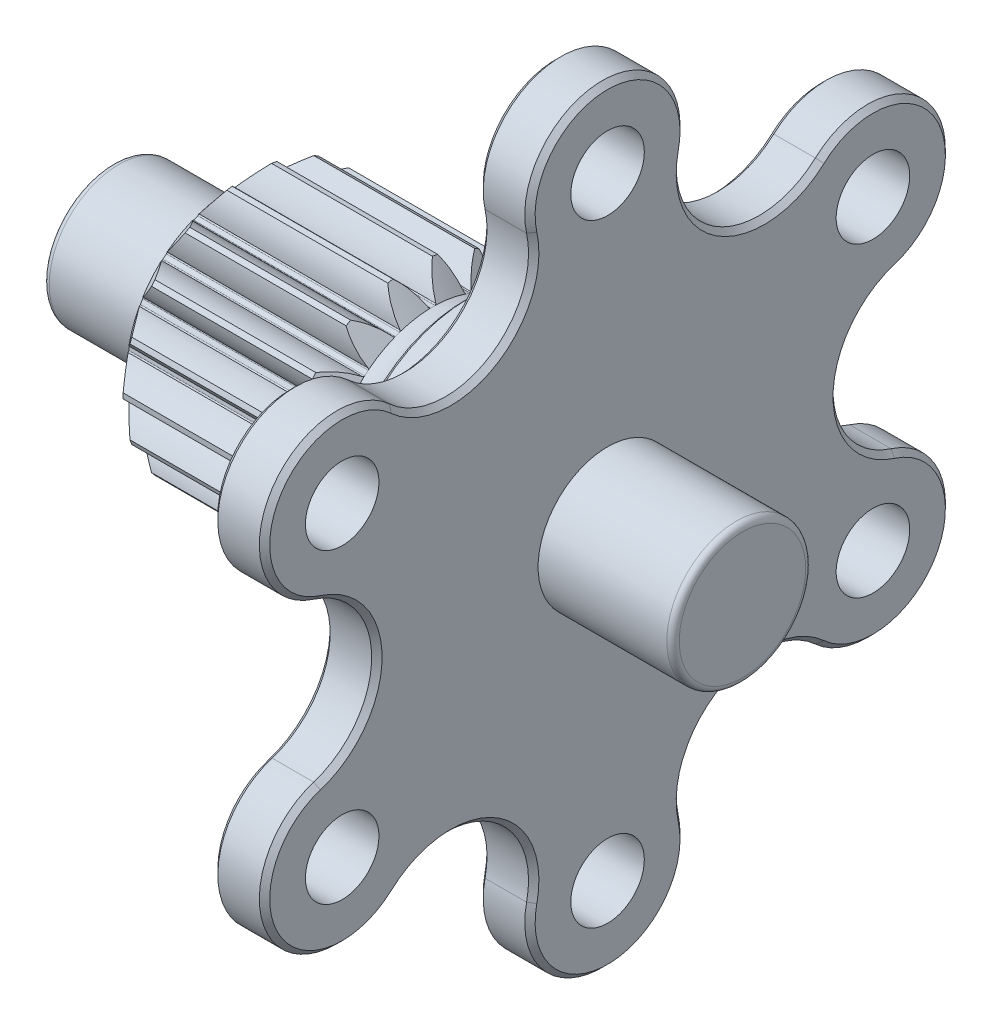
SolidWorks part; units mm, degrees
material "4140 Steel"
ref_plane "X-Y Datum" through (0, 0, 0) normal (0, 0, 1) x (1, 0, 0)
ref_plane "X-Z Datum" through (0, 0, 0) normal (0, 1, 0) x (1, 0, 0)
ref_plane "Y-Z Datum" through (0, 0, 0) normal (1, 0, 0) x (0, 0, -1)
sketch "Sketch1" plane through (0, 0, 0) normal (1, 0, 0) x (0, 0, -1)
  circle A0 centre (0, 0) radius 47
  dimension "D1" = 94
extrude "Base-Extrude" add sketch "Sketch1" against normal blind 6.35
hole_wizard "M8 Clearance Holes" positions "Sketch5" profile "Sketch7" hole size "M8" standard "ANSI Metric" end condition through all
sketch "Sketch5" plane through (0, 0, 0) normal (1, 0, 0) x (0, 0, -1)
  point P0 (0, -37.5)
  dimension "D1" = 37.5
sketch "Sketch7" plane through (0, -37.5, 0) normal (0, 1, 0) x (0, 0, -1)
  line L0 (0, 0) -> (0, 6.35)
  line L1 (0, 6.35) -> (4.5, 6.35)
  line L2 (4.5, 6.35) -> (4.5, 0)
  line L5 (4.5, 0) -> (0, 0)
  line L11 (0, -6.35) -> (0, 107.95) construction
  dimension "Thru Hole Dia." = 9
  dimension "Thru Hole Depth" = 6.35
pattern_circular "CirPattern" count 6 over 360 about axis through (-6.35, 0, 0) along (1, 0, 0) of "M8 Clearance Holes"
sketch "Sketch19" plane through (0, 0, 0) normal (1, 0, 0) x (0, 0, -1)
  line L0 (0, 37.5) -> (32.476, 18.75) construction
  circle A0 centre (0, 37.5) radius 9.5
  circle A1 centre (32.476, 18.75) radius 9.5
  circle A2 centre (0, 0) radius 47 construction
  arc A3 (9.2748, 35.4439) -> (26.0579, 25.7542) centre (19.194, 33.245) ccw
  circle A4 centre (32.476, 18.75) radius 9.5
  circle A5 centre (32.476, -18.75) radius 9.5
  arc A6 (35.3328, 9.6897) -> (35.3328, -9.6897) centre (38.3881, 0) ccw
  circle A7 centre (32.476, -18.75) radius 9.5
  circle A8 centre (0, -37.5) radius 9.5
  arc A9 (26.0579, -25.7542) -> (9.2748, -35.4439) centre (19.194, -33.245) ccw
  circle A10 centre (0, -37.5) radius 9.5
  circle A11 centre (-32.476, -18.75) radius 9.5
  arc A12 (-9.2748, -35.4439) -> (-26.0579, -25.7542) centre (-19.194, -33.245) ccw
  circle A13 centre (-32.476, -18.75) radius 9.5
  circle A14 centre (-32.476, 18.75) radius 9.5
  arc A15 (-35.3328, -9.6897) -> (-35.3328, 9.6897) centre (-38.3881, 0) ccw
  circle A16 centre (-32.476, 18.75) radius 9.5
  circle A17 centre (0, 37.5) radius 9.5
  arc A18 (-26.0579, 25.7542) -> (-9.2748, 35.4439) centre (-19.194, 33.245) ccw
  circle A19 centre (-32.476, 18.75) radius 4.5 construction
  circle M12 centre (0, 0) radius 47
  dimension "D1" = 10.16
  dimension "D2" = 6
extrude "Cut-Extrude" cut sketch "Sketch19" against normal through all both and the other way through all contours A16 A18 A0 M12 | A0 A3 A1 M12 | A13 A15 A14 M12 | A4 A6 A5 M12 | A7 A9 A8 M12 | A10 A12 A11 M12 | L0 A3 region at (0, 34.8675, -20.1307) region at (0, 26.6235, -15.3711) region at (0, 33.8688, 19.5541) region at (0, 0, -39.1083) region at (0, 0, 39.1083) region at (0, -33.8688, 19.5541) region at (0, -33.8688, -19.5541)
chamfer "Chamfer1" distance 0.635 angle 45 12 edges at (-6.35, 0, 28.2281) (-6.35, -23.5, 40.7032) (-6.35, 23.5, 40.7032) (-6.35, -24.4462, 14.114) (-6.35, 24.4462, 14.114) (-6.35, -47, 0) (-6.35, 47, 0) (-6.35, -24.4462, -14.114) (-6.35, -23.5, -40.7032) (-6.35, 0, -28.2281) (-6.35, 23.5, -40.7032) (-6.35, 24.4462, -14.114)
sketch "Sketch8" plane through (-6.35, 0, 0) normal (-1, 0, 0) x (0, 0, 1)
  circle A0 centre (0, 0) radius 15.748
  dimension "D1" = 31.496
extrude "Shaft-Extrude" add sketch "Sketch8" along normal blind 52.582
chamfer "Chamfer3" distance 0.635 angle 45 12 edges at (0, -23.5, 40.7032) (0, 0, 28.2281) (0, -24.4462, 14.114) (0, 23.5, 40.7032) (0, -47, 0) (0, 24.4462, 14.114) (0, -24.4462, -14.114) (0, 47, 0) (0, 24.4462, -14.114) (0, -23.5, -40.7032) (0, 0, -28.2281) (0, 23.5, -40.7032)
chamfer "Shaft Chamfer" distance 1 angle 45 1 edges at (-58.932, 0, 15.748)
sketch "Sketch45" plane through (-58.932, 0, 0) normal (-1, 0, 0) x (0, 0, 1)
  circle A0 centre (0, 0) radius 15.748 construction
  circle A1 centre (0, 0) radius 15.748
  circle A2 centre (0, 0) radius 8.5127
  dimension "D1" = 17.0254
extrude "Cut-Extrude1" cut sketch "Sketch45" against normal blind 12.857
chamfer "Chamfer4" [suppressed] distance 0.254 angle 45
sketch "Sketch51" [suppressed] plane through (-6.35, 0, 0) normal (-1, 0, 0) x (0, 0, 1)
  circle A2 centre (0, 0) radius 13.97
  circle A3 centre (0, 0) radius 13.97
  dimension "D1" = 0
extrude "Boss-Extrude1" [suppressed] add sketch "Sketch51" along normal blind 17.5
sketch "Sketch55" plane through (0, 0, 0) normal (1, 0, 0) x (0, 0, -1)
  circle A0 centre (0, 0) radius 8.5
  dimension "D1" = 17
extrude "Boss-Extrude4" add sketch "Sketch55" along normal blind 16.51
sketch "Sketch56" plane through (-58.932, 0, 0) normal (-1, 0, 0) x (0, 0, 1)
  circle A1 centre (0, 0) radius 8.5127
  circle A4 centre (0, 0) radius 8.5127
  dimension "D1" = 0
extrude "Boss-Extrude5" add sketch "Sketch56" along normal blind 1.643
sketch "Sketch22" [suppressed] plane through (-6.35, 0, 0) normal (-1, 0, 0) x (0, 0, 1)
  circle A0 centre (32.476, 18.75) radius 6.1
  circle A1 centre (32.476, -18.75) radius 6.1
  circle A2 centre (0, -37.5) radius 6.1
  circle A3 centre (0, 37.5) radius 6.1
  circle A4 centre (-32.476, 18.75) radius 6.1
  circle A5 centre (-32.476, -18.75) radius 6.1
  dimension "D1" = 12.2
split line "Split Line1" [suppressed]
split line "Split Line2"
sketch "Sketch22<2>" [suppressed] plane through (-6.35, 0, 0) normal (-1, 0, 0) x (0, 0, 1) same geometry as "Sketch22"
fillet "Fillet4" [suppressed] radius 1.5875
ref_plane "Plane3" [suppressed] through (0, 0, 12.7) normal (0, 0, 1) x (1, 0, 0)
sketch "Sketch48" [suppressed] plane through (0, 0, 12.7) normal (0, 0, 1) x (1, 0, 0)
  line L0 (-46.075, 12.446) -> (-46.075, -12.446) construction
  line L1 (-23.85, 3.175) -> (-46.075, 3.175)
  line L3 (-23.85, -3.175) -> (-46.075, -3.175)
  line L4 (-46.075, 3.175) -> (-46.075, -3.175)
  line L5 (-46.075, 12.446) -> (-46.075, -12.446)
  line L6 (-46.075, 0) -> (-12.2887, 0) construction
  line L7 (-23.85, 12.7) -> (-23.85, -12.7) construction
  arc A0 (-23.85, 3.175) -> (-23.85, -3.175) centre (-23.85, 0) cw
  dimension "D2" = 6.35
extrude "Cut-Extrude3" [suppressed] cut sketch "Sketch48" against normal blind 3.175 and the other way blind 17.5 contours L4 L6 A0 L1 | L6 L5 L3 A0
ref_plane "Plane4" [suppressed] through (0, 0, 13.97) normal (0, 0, 1) x (1, 0, 0)
fillet "Fillet5" [suppressed] radius 0.7937
sketch "Sketch57" [suppressed] plane through (-46.075, 0, 0) normal (-1, 0, 0) x (0, 0, 1)
  arc A0 (9.097, -5.6181) -> (9.7313, -4.4292) centre (0, 0) ccw
  arc A1 (9.097, -5.6181) -> (9.0986, -5.9863) centre (9.3955, -5.8008) ccw
  arc A2 (10.055, -4.164) -> (9.7313, -4.4292) centre (10.071, -4.5136) ccw
  arc A3 (12.1705, -3.6562) -> (12.3682, -3.3733) centre (12.0198, -3.3403) ccw
  arc A4 (12.3682, -3.3733) -> (12.5192, -2.7609) centre (0, 0) ccw
  arc A5 (9.3839, -8.7347) -> (9.8021, -8.2626) centre (0, 0) ccw
  arc A6 (4.2498, -12.0951) -> (4.8395, -11.8715) centre (0, 0) ccw
  arc A7 (-1.8579, -12.6847) -> (-1.2318, -12.7607) centre (0, 0) ccw
  arc A8 (-7.5399, -10.3683) -> (-7.0209, -10.7266) centre (0, 0) ccw
  arc A9 (-11.4947, -5.6767) -> (-11.2016, -6.2352) centre (0, 0) ccw
  arc A10 (-12.82, 0) -> (-12.8161, -0.3154) centre (0, 0) ccw
  arc A11 (12.5274, -2.6855) -> (12.4465, -2.4617) centre (12.1774, -2.6855) ccw
  arc A12 (12.5192, -2.7609) -> (12.5274, -2.6855) centre (12.1774, -2.6855) ccw
  arc A13 (10.6367, -0.7037) -> (10.8093, -1.029) centre (10.986, -0.7268) ccw
  arc A14 (10.6367, -0.7037) -> (10.66, 0) centre (0, 0) ccw
  arc A15 (10.66, 0) -> (10.6367, 0.7037) centre (0, 0) ccw
  arc A16 (10.8093, 1.029) -> (10.6367, 0.7037) centre (10.986, 0.7268) ccw
  arc A17 (12.4465, 2.4617) -> (12.5274, 2.6855) centre (12.1774, 2.6855) ccw
  arc A18 (-12.8161, 0.3154) -> (-12.82, 0) centre (0, 0) ccw
  arc A19 (-11.2016, 6.2352) -> (-11.4947, 5.6767) centre (0, 0) ccw
  arc A20 (-7.0209, 10.7266) -> (-7.5399, 10.3683) centre (0, 0) ccw
  arc A21 (-1.2318, 12.7607) -> (-1.8579, 12.6847) centre (0, 0) ccw
  arc A22 (4.8395, 11.8715) -> (4.2498, 12.0951) centre (0, 0) ccw
  arc A23 (9.8021, 8.2626) -> (9.3839, 8.7347) centre (0, 0) ccw
  arc A24 (12.5192, 2.7609) -> (12.3682, 3.3733) centre (0, 0) ccw
  arc A25 (12.5274, 2.6855) -> (12.5192, 2.7609) centre (12.1774, 2.6855) ccw
  arc A26 (12.3682, 3.3733) -> (12.1649, 3.6044) centre (12.0306, 3.2812) ccw
  arc A27 (9.7454, 4.32) -> (10.0494, 4.1122) centre (10.0654, 4.4619) ccw
  arc A28 (9.7454, 4.32) -> (9.0913, 5.5663) centre (0, 0) ccw
  arc A29 (9.093, 5.9345) -> (9.0913, 5.5663) centre (9.3898, 5.749) ccw
  arc A30 (9.8845, 8.037) -> (9.8021, 8.2626) centre (9.5345, 8.037) ccw
  arc A31 (9.8768, 7.9639) -> (9.8845, 8.037) centre (9.5345, 8.037) ccw
  arc A32 (9.3839, 8.7347) -> (9.0964, 8.8448) centre (9.1277, 8.4962) ccw
  arc A33 (6.6215, 8.3541) -> (5.4632, 9.1536) centre (0, 0) ccw
  arc A34 (6.6215, 8.3541) -> (6.9873, 8.3114) centre (6.8389, 8.6284) ccw
  arc A35 (5.2936, 9.4805) -> (5.4632, 9.1536) centre (5.6426, 9.4542) ccw
  arc A36 (5.0444, 11.6417) -> (4.8395, 11.8715) centre (4.7074, 11.5474) ccw
  arc A37 (4.2498, 12.0951) -> (3.9441, 12.059) centre (4.1338, 11.7649) ccw
  arc A38 (1.9807, 10.4744) -> (0.5835, 10.644) centre (0, 0) ccw
  arc A39 (1.9807, 10.4744) -> (2.3244, 10.6065) centre (2.0458, 10.8183) ccw
  arc A40 (0.2814, 10.8546) -> (0.5835, 10.644) centre (0.6027, 10.9935) ccw
  arc A41 (-0.9435, 12.6525) -> (-1.2318, 12.7607) centre (-1.1981, 12.4123) ccw
  arc A42 (-1.8579, 12.6847) -> (-2.1118, 12.5106) centre (-1.8071, 12.3384) ccw
  arc A43 (-3.1138, 10.1951) -> (-4.4298, 9.696) centre (0, 0) ccw
  arc A44 (-3.1138, 10.1951) -> (-2.8709, 10.4718) centre (-3.2161, 10.5298) ccw
  arc A45 (-4.7952, 9.742) -> (-4.4298, 9.696) centre (-4.5753, 10.0143) ccw
  arc A46 (-6.7154, 10.7647) -> (-7.0209, 10.7266) centre (-6.8292, 10.4338) ccw
  arc A47 (-7.5399, 10.3683) -> (-7.6839, 10.0962) centre (-7.3341, 10.0853) ccw
  arc A48 (-7.4951, 7.5802) -> (-7.3911, 7.8291) centre (-7.7411, 7.8291) ccw
  arc A49 (-7.4951, 7.5802) -> (-8.4284, 6.5267) centre (0, 0) ccw
  arc A50 (-7.3911, 7.8291) -> (-7.4086, 7.9381) centre (-7.7411, 7.8291) ccw
  arc A51 (-8.7733, 6.3977) -> (-8.4284, 6.5267) centre (-8.7051, 6.741) ccw
  arc A52 (-10.9488, 6.4109) -> (-11.2016, 6.2352) centre (-10.8957, 6.065) ccw
  arc A53 (-11.4947, 5.6767) -> (-11.4957, 5.3689) centre (-11.1808, 5.5217) ccw
  arc A54 (-10.1592, 3.2288) -> (-10.4961, 1.8623) centre (0, 0) ccw
  arc A55 (-10.1428, 3.3348) -> (-10.249, 3.5859) centre (-10.4928, 3.3348) ccw
  arc A56 (-10.1592, 3.2288) -> (-10.1428, 3.3348) centre (-10.4928, 3.3348) ccw
  arc A57 (-10.7415, 1.5877) -> (-10.4961, 1.8623) centre (-10.8407, 1.9234) ccw
  arc A58 (-12.674, 0.5884) -> (-12.8161, 0.3154) centre (-12.4662, 0.3067) ccw
  arc A59 (-12.8161, -0.3154) -> (-12.674, -0.5884) centre (-12.4662, -0.3067) ccw
  arc A60 (-10.4961, -1.8623) -> (-10.7415, -1.5877) centre (-10.8407, -1.9234) ccw
  arc A61 (-10.4961, -1.8623) -> (-10.1592, -3.2288) centre (0, 0) ccw
  arc A62 (-10.1428, -3.3348) -> (-10.1592, -3.2288) centre (-10.4928, -3.3348) ccw
  arc A63 (-10.249, -3.5859) -> (-10.1428, -3.3348) centre (-10.4928, -3.3348) ccw
  arc A64 (-11.4957, -5.3689) -> (-11.4947, -5.6767) centre (-11.1808, -5.5217) ccw
  arc A65 (-11.2016, -6.2352) -> (-10.9488, -6.4109) centre (-10.8957, -6.065) ccw
  arc A66 (-8.4284, -6.5267) -> (-8.7733, -6.3977) centre (-8.7051, -6.741) ccw
  arc A67 (-8.4284, -6.5267) -> (-7.4951, -7.5802) centre (0, 0) ccw
  arc A68 (-7.3911, -7.8291) -> (-7.4951, -7.5802) centre (-7.7411, -7.8291) ccw
  arc A69 (-7.4086, -7.9381) -> (-7.3911, -7.8291) centre (-7.7411, -7.8291) ccw
  arc A70 (-7.6839, -10.0962) -> (-7.5399, -10.3683) centre (-7.3341, -10.0853) ccw
  arc A71 (-7.0209, -10.7266) -> (-6.7154, -10.7647) centre (-6.8292, -10.4338) ccw
  arc A72 (-4.4298, -9.696) -> (-4.7952, -9.742) centre (-4.5753, -10.0143) ccw
  arc A73 (-4.4298, -9.696) -> (-3.1138, -10.1951) centre (0, 0) ccw
  arc A74 (-2.8709, -10.4718) -> (-3.1138, -10.1951) centre (-3.2161, -10.5298) ccw
  arc A75 (-2.1118, -12.5106) -> (-1.8579, -12.6847) centre (-1.8071, -12.3384) ccw
  arc A76 (-1.2318, -12.7607) -> (-0.9435, -12.6525) centre (-1.1981, -12.4123) ccw
  arc A77 (0.5835, -10.644) -> (1.9807, -10.4744) centre (0, 0) ccw
  arc A78 (0.5835, -10.644) -> (0.2814, -10.8546) centre (0.6027, -10.9935) ccw
  arc A79 (2.3244, -10.6065) -> (1.9807, -10.4744) centre (2.0458, -10.8183) ccw
  arc A80 (3.9441, -12.059) -> (4.2498, -12.0951) centre (4.1338, -11.7649) ccw
  arc A81 (4.8395, -11.8715) -> (5.0444, -11.6417) centre (4.7074, -11.5474) ccw
  arc A82 (5.4632, -9.1536) -> (5.2936, -9.4805) centre (5.6426, -9.4542) ccw
  arc A83 (5.4632, -9.1536) -> (6.6215, -8.3541) centre (0, 0) ccw
  arc A84 (6.9873, -8.3114) -> (6.6215, -8.3541) centre (6.8389, -8.6284) ccw
  arc A85 (9.0964, -8.8448) -> (9.3839, -8.7347) centre (9.1277, -8.4962) ccw
  arc A86 (9.8021, -8.2626) -> (9.8901, -8.0888) centre (9.5462, -8.0238) ccw
  arc A87 (9.8901, -8.0888) -> (9.8824, -8.0157) centre (9.5401, -8.0888) ccw
  circle A88 centre (0, 0) radius 13.97 construction
  circle A89 centre (0, 0) radius 13.97
  spline S0 degree 4 poles (9.0986, -5.9863) (9.1513, -6.0706) (9.2437, -6.2285) (9.367, -6.4648) (9.5091, -6.7844) (9.6282, -7.0962) (9.741, -7.4422) (9.814, -7.7129) (9.8587, -7.9047) (9.8824, -8.0157) knots 0 0 0 0 0 0.181969 0.334561 0.487154 0.639745 0.792337 1 1 1 1 1 weights 1 1 1 1 1 1 1 1 1 1
  spline S1 degree 4 poles (10.055, -4.164) (10.1544, -4.1595) (10.3368, -4.1458) (10.6013, -4.113) (10.9451, -4.0484) (11.2693, -3.9693) (11.6181, -3.8656) (11.8824, -3.7718) (12.0657, -3.6997) (12.1705, -3.6562) knots 0 0 0 0 0 0.181969 0.334561 0.487154 0.639745 0.792337 1 1 1 1 1 weights 1 1 1 1 1 1 1 1 1 1
  spline S2 degree 4 poles (10.8093, -1.029) (10.8952, -1.0792) (11.0504, -1.176) (11.2693, -1.328) (11.5437, -1.545) (11.7941, -1.7657) (12.0547, -2.0196) (12.2452, -2.2255) (12.3739, -2.3745) (12.4465, -2.4617) knots 0 0 0 0 0 0.181969 0.334561 0.487154 0.639745 0.792337 1 1 1 1 1 weights 1 1 1 1 1 1 1 1 1 1
  spline S3 degree 4 poles (10.8093, 1.029) (10.8952, 1.0792) (11.0504, 1.176) (11.2693, 1.328) (11.5437, 1.545) (11.7941, 1.7657) (12.0547, 2.0196) (12.2452, 2.2255) (12.3739, 2.3745) (12.4465, 2.4617) knots 0 0 0 0 0 0.181969 0.334561 0.487154 0.639745 0.792337 1 1 1 1 1 weights 1 1 1 1 1 1 1 1 1 1
  spline S4 degree 4 poles (10.0494, 4.1122) (10.1488, 4.1077) (10.3312, 4.094) (10.5956, 4.0613) (10.9394, 3.9966) (11.2637, 3.9175) (11.6125, 3.8138) (11.8768, 3.7201) (12.06, 3.648) (12.1649, 3.6044) knots 0 0 0 0 0 0.181969 0.334561 0.487154 0.639745 0.792337 1 1 1 1 1 weights 1 1 1 1 1 1 1 1 1 1
  spline S5 degree 4 poles (9.093, 5.9345) (9.1457, 6.0188) (9.2381, 6.1767) (9.3613, 6.413) (9.5035, 6.7326) (9.6225, 7.0445) (9.7353, 7.3904) (9.8083, 7.6612) (9.8531, 7.8529) (9.8768, 7.9639) knots 0 0 0 0 0 0.181969 0.334561 0.487154 0.639745 0.792337 1 1 1 1 1 weights 1 1 1 1 1 1 1 1 1 1
  spline S6 degree 4 poles (6.9873, 8.3114) (7.0773, 8.3535) (7.2452, 8.4262) (7.4946, 8.5201) (7.8291, 8.6227) (8.153, 8.7033) (8.51, 8.7735) (8.7876, 8.8134) (8.9833, 8.8347) (9.0964, 8.8448) knots 0 0 0 0 0 0.181969 0.334561 0.487154 0.639745 0.792337 1 1 1 1 1 weights 1 1 1 1 1 1 1 1 1 1
  spline S7 degree 4 poles (5.2936, 9.4805) (5.301, 9.5796) (5.3095, 9.7624) (5.3088, 10.0288) (5.2861, 10.3779) (5.2466, 10.7094) (5.1857, 11.0681) (5.1245, 11.3418) (5.075, 11.5324) (5.0444, 11.6417) knots 0 0 0 0 0 0.181969 0.334561 0.487154 0.639745 0.792337 1 1 1 1 1 weights 1 1 1 1 1 1 1 1 1 1
  spline S8 degree 4 poles (2.3244, 10.6065) (2.3846, 10.6857) (2.4995, 10.8281) (2.6767, 11.0271) (2.9252, 11.2733) (3.1745, 11.4952) (3.4579, 11.7234) (3.6852, 11.8876) (3.8487, 11.9975) (3.9441, 12.059) knots 0 0 0 0 0 0.181969 0.334561 0.487154 0.639745 0.792337 1 1 1 1 1 weights 1 1 1 1 1 1 1 1 1 1
  spline S9 degree 4 poles (0.2814, 10.8546) (0.2419, 10.9458) (0.1645, 11.1116) (0.0401, 11.3472) (-0.1423, 11.6458) (-0.3313, 11.9209) (-0.5519, 12.2102) (-0.7332, 12.4241) (-0.8657, 12.5699) (-0.9435, 12.6525) knots 0 0 0 0 0 0.181969 0.334561 0.487154 0.639745 0.792337 1 1 1 1 1 weights 1 1 1 1 1 1 1 1 1 1
  spline S10 degree 4 poles (-2.8709, 10.4718) (-2.8544, 10.5699) (-2.8189, 10.7493) (-2.7545, 11.0079) (-2.6489, 11.3414) (-2.5312, 11.6538) (-2.3863, 11.9875) (-2.2613, 12.2386) (-2.1677, 12.4118) (-2.1118, 12.5106) knots 0 0 0 0 0 0.181969 0.334561 0.487154 0.639745 0.792337 1 1 1 1 1 weights 1 1 1 1 1 1 1 1 1 1
  spline S11 degree 4 poles (-4.7952, 9.742) (-4.8726, 9.8045) (-5.0181, 9.9153) (-5.2378, 10.0661) (-5.538, 10.2457) (-5.8332, 10.4015) (-6.163, 10.5552) (-6.423, 10.6603) (-6.608, 10.7278) (-6.7154, 10.7647) knots 0 0 0 0 0 0.181969 0.334561 0.487154 0.639745 0.792337 1 1 1 1 1 weights 1 1 1 1 1 1 1 1 1 1
  spline S12 degree 4 poles (-7.4086, 7.9381) (-7.4395, 8.0326) (-7.4915, 8.2081) (-7.5546, 8.4669) (-7.6161, 8.8113) (-7.6571, 9.1426) (-7.6838, 9.5054) (-7.6899, 9.7858) (-7.6874, 9.9827) (-7.6839, 10.0962) knots 0 0 0 0 0 0.181969 0.334561 0.487154 0.639745 0.792337 1 1 1 1 1 weights 1 1 1 1 1 1 1 1 1 1
  spline S13 degree 4 poles (-8.7733, 6.3977) (-8.8708, 6.4171) (-9.0512, 6.4475) (-9.3158, 6.4789) (-9.6651, 6.4985) (-9.9989, 6.4992) (-10.3623, 6.482) (-10.6414, 6.4543) (-10.8366, 6.4281) (-10.9488, 6.4109) knots 0 0 0 0 0 0.181969 0.334561 0.487154 0.639745 0.792337 1 1 1 1 1 weights 1 1 1 1 1 1 1 1 1 1
  spline S14 degree 4 poles (-10.249, 3.5859) (-10.3203, 3.6552) (-10.4478, 3.7864) (-10.624, 3.9863) (-10.8386, 4.2627) (-11.0288, 4.5369) (-11.2211, 4.8458) (-11.3567, 5.0913) (-11.4461, 5.2667) (-11.4957, 5.3689) knots 0 0 0 0 0 0.181969 0.334561 0.487154 0.639745 0.792337 1 1 1 1 1 weights 1 1 1 1 1 1 1 1 1 1
  spline S15 degree 4 poles (-10.7415, 1.5877) (-10.8369, 1.5596) (-11.0107, 1.5027) (-11.2597, 1.4075) (-11.578, 1.2625) (-11.8739, 1.1081) (-12.1877, 0.9239) (-12.4219, 0.7697) (-12.5826, 0.6558) (-12.674, 0.5884) knots 0 0 0 0 0 0.181969 0.334561 0.487154 0.639745 0.792337 1 1 1 1 1 weights 1 1 1 1 1 1 1 1 1 1
  spline S16 degree 4 poles (-10.7415, -1.5877) (-10.8369, -1.5596) (-11.0107, -1.5027) (-11.2597, -1.4075) (-11.578, -1.2625) (-11.8739, -1.1081) (-12.1877, -0.9239) (-12.4219, -0.7697) (-12.5826, -0.6558) (-12.674, -0.5884) knots 0 0 0 0 0 0.181969 0.334561 0.487154 0.639745 0.792337 1 1 1 1 1 weights 1 1 1 1 1 1 1 1 1 1
  spline S17 degree 4 poles (-10.249, -3.5859) (-10.3203, -3.6552) (-10.4478, -3.7864) (-10.624, -3.9863) (-10.8386, -4.2627) (-11.0288, -4.5369) (-11.2211, -4.8458) (-11.3567, -5.0913) (-11.4461, -5.2667) (-11.4957, -5.3689) knots 0 0 0 0 0 0.181969 0.334561 0.487154 0.639745 0.792337 1 1 1 1 1 weights 1 1 1 1 1 1 1 1 1 1
  spline S18 degree 4 poles (-8.7733, -6.3977) (-8.8708, -6.4171) (-9.0512, -6.4475) (-9.3158, -6.4789) (-9.6651, -6.4985) (-9.9989, -6.4992) (-10.3623, -6.482) (-10.6414, -6.4543) (-10.8366, -6.4281) (-10.9488, -6.4109) knots 0 0 0 0 0 0.181969 0.334561 0.487154 0.639745 0.792337 1 1 1 1 1 weights 1 1 1 1 1 1 1 1 1 1
  spline S19 degree 4 poles (-7.4086, -7.9381) (-7.4395, -8.0326) (-7.4915, -8.2081) (-7.5546, -8.4669) (-7.6161, -8.8113) (-7.6571, -9.1426) (-7.6838, -9.5054) (-7.6899, -9.7858) (-7.6874, -9.9827) (-7.6839, -10.0962) knots 0 0 0 0 0 0.181969 0.334561 0.487154 0.639745 0.792337 1 1 1 1 1 weights 1 1 1 1 1 1 1 1 1 1
  spline S20 degree 4 poles (-4.7952, -9.742) (-4.8726, -9.8045) (-5.0181, -9.9153) (-5.2378, -10.0661) (-5.538, -10.2457) (-5.8332, -10.4015) (-6.163, -10.5552) (-6.423, -10.6603) (-6.608, -10.7278) (-6.7154, -10.7647) knots 0 0 0 0 0 0.181969 0.334561 0.487154 0.639745 0.792337 1 1 1 1 1 weights 1 1 1 1 1 1 1 1 1 1
  spline S21 degree 4 poles (-2.8709, -10.4718) (-2.8544, -10.5699) (-2.8189, -10.7493) (-2.7545, -11.0079) (-2.6489, -11.3414) (-2.5312, -11.6538) (-2.3863, -11.9875) (-2.2613, -12.2386) (-2.1677, -12.4118) (-2.1118, -12.5106) knots 0 0 0 0 0 0.181969 0.334561 0.487154 0.639745 0.792337 1 1 1 1 1 weights 1 1 1 1 1 1 1 1 1 1
  spline S22 degree 4 poles (0.2814, -10.8546) (0.2419, -10.9458) (0.1645, -11.1116) (0.0401, -11.3472) (-0.1423, -11.6458) (-0.3313, -11.9209) (-0.5519, -12.2102) (-0.7332, -12.4241) (-0.8657, -12.5699) (-0.9435, -12.6525) knots 0 0 0 0 0 0.181969 0.334561 0.487154 0.639745 0.792337 1 1 1 1 1 weights 1 1 1 1 1 1 1 1 1 1
  spline S23 degree 4 poles (2.3244, -10.6065) (2.3846, -10.6857) (2.4995, -10.8281) (2.6767, -11.0271) (2.9252, -11.2733) (3.1745, -11.4952) (3.4579, -11.7234) (3.6852, -11.8876) (3.8487, -11.9975) (3.9441, -12.059) knots 0 0 0 0 0 0.181969 0.334561 0.487154 0.639745 0.792337 1 1 1 1 1 weights 1 1 1 1 1 1 1 1 1 1
  spline S24 degree 4 poles (5.2936, -9.4805) (5.301, -9.5796) (5.3095, -9.7624) (5.3088, -10.0288) (5.2861, -10.3779) (5.2466, -10.7094) (5.1857, -11.0681) (5.1245, -11.3418) (5.075, -11.5324) (5.0444, -11.6417) knots 0 0 0 0 0 0.181969 0.334561 0.487154 0.639745 0.792337 1 1 1 1 1 weights 1 1 1 1 1 1 1 1 1 1
  spline S25 degree 4 poles (6.9873, -8.3114) (7.0773, -8.3535) (7.2452, -8.4262) (7.4946, -8.5201) (7.8291, -8.6227) (8.153, -8.7033) (8.51, -8.7735) (8.7876, -8.8134) (8.9833, -8.8347) (9.0964, -8.8448) knots 0 0 0 0 0 0.181969 0.334561 0.487154 0.639745 0.792337 1 1 1 1 1 weights 1 1 1 1 1 1 1 1 1 1
extrude "Cut-Extrude6" [suppressed] cut sketch "Sketch57" against normal blind 22.225
sketch "Sketch58" [suppressed] plane through (-23.85, 0, 0) normal (-1, 0, 0) x (0, 0, 1)
  circle A0 centre (0, 0) radius 12.7679
  circle A1 centre (0, 0) radius 13.97 construction
  circle A2 centre (0, 0) radius 13.97
extrude "Cut-Extrude7" [suppressed] cut sketch "Sketch58" against normal up to surface (17.5 mm away) up to face at (-6.35, 0, -15.748)
sketch "Sketch59" [suppressed] plane through (-23.85, 0, 0) normal (-1, 0, 0) x (0, 0, 1)
  circle A1 centre (0, 0) radius 12.7679 construction
  circle A2 centre (0, 0) radius 12.7679
  circle A7 centre (0, 0) radius 10.541
  dimension "D1" = 21.082
extrude "Cut-Extrude10" [suppressed] cut sketch "Sketch59" against normal blind 3.175
chamfer "Chamfer5" [suppressed] distance 1.524 angle 45
sketch "Sketch65" [suppressed] plane through (-46.075, 0, 0) normal (-1, 0, 0) x (0, 0, 1)
  arc A3 (9.097, -5.6181) -> (9.0986, -5.9863) centre (9.3955, -5.8008) ccw
  arc A84 (9.097, -5.6181) -> (9.0986, -5.9863) centre (9.3955, -5.8008) ccw
  arc A85 (9.097, -5.6181) -> (9.7313, -4.4292) centre (0, 0) ccw
  arc A86 (9.097, -5.6181) -> (9.7313, -4.4292) centre (0, 0) ccw
  arc A87 (10.055, -4.164) -> (9.7313, -4.4292) centre (10.071, -4.5136) ccw
  arc A88 (10.055, -4.164) -> (9.7313, -4.4292) centre (10.071, -4.5136) ccw
  arc A89 (12.1705, -3.6562) -> (12.3682, -3.3733) centre (12.0198, -3.3403) ccw
  arc A90 (12.1705, -3.6562) -> (12.3682, -3.3733) centre (12.0198, -3.3403) ccw
  arc A91 (12.3682, -3.3733) -> (12.5192, -2.7609) centre (0, 0) ccw
  arc A92 (12.3682, -3.3733) -> (12.5192, -2.7609) centre (0, 0) ccw
  arc A93 (12.5192, -2.7609) -> (12.4465, -2.4617) centre (12.1774, -2.6855) ccw
  arc A94 (12.5192, -2.7609) -> (12.4465, -2.4617) centre (12.1774, -2.6855) ccw
  arc A95 (10.6367, -0.7037) -> (10.8093, -1.029) centre (10.986, -0.7268) ccw
  arc A96 (10.6367, -0.7037) -> (10.8093, -1.029) centre (10.986, -0.7268) ccw
  arc A97 (10.6367, -0.7037) -> (10.6367, 0.7037) centre (0, 0) ccw
  arc A98 (10.6367, -0.7037) -> (10.6367, 0.7037) centre (0, 0) ccw
  arc A99 (10.8093, 1.029) -> (10.6367, 0.7037) centre (10.986, 0.7268) ccw
  arc A100 (10.8093, 1.029) -> (10.6367, 0.7037) centre (10.986, 0.7268) ccw
  arc A101 (12.4465, 2.4617) -> (12.5192, 2.7609) centre (12.1774, 2.6855) ccw
  arc A102 (12.4465, 2.4617) -> (12.5192, 2.7609) centre (12.1774, 2.6855) ccw
  arc A103 (12.5192, 2.7609) -> (12.3682, 3.3733) centre (0, 0) ccw
  arc A104 (12.5192, 2.7609) -> (12.3682, 3.3733) centre (0, 0) ccw
  arc A105 (12.3682, 3.3733) -> (12.1649, 3.6044) centre (12.0306, 3.2812) ccw
  arc A106 (12.3682, 3.3733) -> (12.1649, 3.6044) centre (12.0306, 3.2812) ccw
  arc A107 (9.7454, 4.32) -> (10.0494, 4.1122) centre (10.0654, 4.4619) ccw
  arc A108 (9.7454, 4.32) -> (10.0494, 4.1122) centre (10.0654, 4.4619) ccw
  arc A109 (9.7454, 4.32) -> (9.0913, 5.5663) centre (0, 0) ccw
  arc A110 (9.7454, 4.32) -> (9.0913, 5.5663) centre (0, 0) ccw
  arc A111 (9.093, 5.9345) -> (9.0913, 5.5663) centre (9.3898, 5.749) ccw
  arc A112 (9.093, 5.9345) -> (9.0913, 5.5663) centre (9.3898, 5.749) ccw
  arc A113 (9.8768, 7.9639) -> (9.8021, 8.2626) centre (9.5345, 8.037) ccw
  arc A114 (9.8768, 7.9639) -> (9.8021, 8.2626) centre (9.5345, 8.037) ccw
  arc A115 (9.8021, 8.2626) -> (9.3839, 8.7347) centre (0, 0) ccw
  arc A116 (9.8021, 8.2626) -> (9.3839, 8.7347) centre (0, 0) ccw
  arc A117 (9.3839, 8.7347) -> (9.0964, 8.8448) centre (9.1277, 8.4962) ccw
  arc A118 (9.3839, 8.7347) -> (9.0964, 8.8448) centre (9.1277, 8.4962) ccw
  arc A119 (6.6215, 8.3541) -> (6.9873, 8.3114) centre (6.8389, 8.6284) ccw
  arc A120 (6.6215, 8.3541) -> (6.9873, 8.3114) centre (6.8389, 8.6284) ccw
  arc A121 (6.6215, 8.3541) -> (5.4632, 9.1536) centre (0, 0) ccw
  arc A122 (6.6215, 8.3541) -> (5.4632, 9.1536) centre (0, 0) ccw
  arc A123 (5.2936, 9.4805) -> (5.4632, 9.1536) centre (5.6426, 9.4542) ccw
  arc A124 (5.2936, 9.4805) -> (5.4632, 9.1536) centre (5.6426, 9.4542) ccw
  arc A125 (5.0444, 11.6417) -> (4.8395, 11.8715) centre (4.7074, 11.5474) ccw
  arc A126 (5.0444, 11.6417) -> (4.8395, 11.8715) centre (4.7074, 11.5474) ccw
  arc A127 (4.8395, 11.8715) -> (4.2498, 12.0951) centre (0, 0) ccw
  arc A128 (4.8395, 11.8715) -> (4.2498, 12.0951) centre (0, 0) ccw
  arc A129 (4.2498, 12.0951) -> (3.9441, 12.059) centre (4.1338, 11.7649) ccw
  arc A130 (4.2498, 12.0951) -> (3.9441, 12.059) centre (4.1338, 11.7649) ccw
  arc A131 (1.9807, 10.4744) -> (2.3244, 10.6065) centre (2.0458, 10.8183) ccw
  arc A132 (1.9807, 10.4744) -> (2.3244, 10.6065) centre (2.0458, 10.8183) ccw
  arc A133 (1.9807, 10.4744) -> (0.5835, 10.644) centre (0, 0) ccw
  arc A134 (1.9807, 10.4744) -> (0.5835, 10.644) centre (0, 0) ccw
  arc A135 (0.2814, 10.8546) -> (0.5835, 10.644) centre (0.6027, 10.9935) ccw
  arc A136 (0.2814, 10.8546) -> (0.5835, 10.644) centre (0.6027, 10.9935) ccw
  arc A137 (-0.9435, 12.6525) -> (-1.2318, 12.7607) centre (-1.1981, 12.4123) ccw
  arc A138 (-0.9435, 12.6525) -> (-1.2318, 12.7607) centre (-1.1981, 12.4123) ccw
  arc A139 (-1.2318, 12.7607) -> (-1.8579, 12.6847) centre (0, 0) ccw
  arc A140 (-1.2318, 12.7607) -> (-1.8579, 12.6847) centre (0, 0) ccw
  arc A141 (-1.8579, 12.6847) -> (-2.1118, 12.5106) centre (-1.8071, 12.3384) ccw
  arc A142 (-1.8579, 12.6847) -> (-2.1118, 12.5106) centre (-1.8071, 12.3384) ccw
  arc A143 (-3.1138, 10.1951) -> (-2.8709, 10.4718) centre (-3.2161, 10.5298) ccw
  arc A144 (-3.1138, 10.1951) -> (-2.8709, 10.4718) centre (-3.2161, 10.5298) ccw
  arc A145 (-3.1138, 10.1951) -> (-4.4298, 9.696) centre (0, 0) ccw
  arc A146 (-3.1138, 10.1951) -> (-4.4298, 9.696) centre (0, 0) ccw
  arc A147 (-4.7952, 9.742) -> (-4.4298, 9.696) centre (-4.5753, 10.0143) ccw
  arc A148 (-4.7952, 9.742) -> (-4.4298, 9.696) centre (-4.5753, 10.0143) ccw
  arc A149 (-6.7154, 10.7647) -> (-7.0209, 10.7266) centre (-6.8292, 10.4338) ccw
  arc A150 (-6.7154, 10.7647) -> (-7.0209, 10.7266) centre (-6.8292, 10.4338) ccw
  arc A151 (-7.0209, 10.7266) -> (-7.5399, 10.3683) centre (0, 0) ccw
  arc A152 (-7.0209, 10.7266) -> (-7.5399, 10.3683) centre (0, 0) ccw
  arc A153 (-7.5399, 10.3683) -> (-7.6839, 10.0962) centre (-7.3341, 10.0853) ccw
  arc A154 (-7.5399, 10.3683) -> (-7.6839, 10.0962) centre (-7.3341, 10.0853) ccw
  arc A155 (-7.4951, 7.5802) -> (-7.4086, 7.9381) centre (-7.7411, 7.8291) ccw
  arc A156 (-7.4951, 7.5802) -> (-7.4086, 7.9381) centre (-7.7411, 7.8291) ccw
  arc A157 (-7.4951, 7.5802) -> (-8.4284, 6.5267) centre (0, 0) ccw
  arc A158 (-7.4951, 7.5802) -> (-8.4284, 6.5267) centre (0, 0) ccw
  arc A159 (-8.7733, 6.3977) -> (-8.4284, 6.5267) centre (-8.7051, 6.741) ccw
  arc A160 (-8.7733, 6.3977) -> (-8.4284, 6.5267) centre (-8.7051, 6.741) ccw
  arc A161 (-10.9488, 6.4109) -> (-11.2016, 6.2352) centre (-10.8957, 6.065) ccw
  arc A162 (-10.9488, 6.4109) -> (-11.2016, 6.2352) centre (-10.8957, 6.065) ccw
  arc A163 (-11.2016, 6.2352) -> (-11.4947, 5.6767) centre (0, 0) ccw
  arc A164 (-11.2016, 6.2352) -> (-11.4947, 5.6767) centre (0, 0) ccw
  arc A165 (-11.4947, 5.6767) -> (-11.4957, 5.3689) centre (-11.1808, 5.5217) ccw
  arc A166 (-11.4947, 5.6767) -> (-11.4957, 5.3689) centre (-11.1808, 5.5217) ccw
  arc A167 (-10.1592, 3.2288) -> (-10.249, 3.5859) centre (-10.4928, 3.3348) ccw
  arc A168 (-10.1592, 3.2288) -> (-10.249, 3.5859) centre (-10.4928, 3.3348) ccw
  arc A169 (-10.1592, 3.2288) -> (-10.4961, 1.8623) centre (0, 0) ccw
  arc A170 (-10.1592, 3.2288) -> (-10.4961, 1.8623) centre (0, 0) ccw
  arc A171 (-10.7415, 1.5877) -> (-10.4961, 1.8623) centre (-10.8407, 1.9234) ccw
  arc A172 (-10.7415, 1.5877) -> (-10.4961, 1.8623) centre (-10.8407, 1.9234) ccw
  arc A173 (-12.674, 0.5884) -> (-12.8161, 0.3154) centre (-12.4662, 0.3067) ccw
  arc A174 (-12.674, 0.5884) -> (-12.8161, 0.3154) centre (-12.4662, 0.3067) ccw
  arc A175 (-12.8161, 0.3154) -> (-12.8161, -0.3154) centre (0, 0) ccw
  arc A176 (-12.8161, 0.3154) -> (-12.8161, -0.3154) centre (0, 0) ccw
  arc A177 (-12.8161, -0.3154) -> (-12.674, -0.5884) centre (-12.4662, -0.3067) ccw
  arc A178 (-12.8161, -0.3154) -> (-12.674, -0.5884) centre (-12.4662, -0.3067) ccw
  arc A179 (-10.4961, -1.8623) -> (-10.7415, -1.5877) centre (-10.8407, -1.9234) ccw
  arc A180 (-10.4961, -1.8623) -> (-10.7415, -1.5877) centre (-10.8407, -1.9234) ccw
  arc A181 (-10.4961, -1.8623) -> (-10.1592, -3.2288) centre (0, 0) ccw
  arc A182 (-10.4961, -1.8623) -> (-10.1592, -3.2288) centre (0, 0) ccw
  arc A183 (-10.249, -3.5859) -> (-10.1592, -3.2288) centre (-10.4928, -3.3348) ccw
  arc A184 (-10.249, -3.5859) -> (-10.1592, -3.2288) centre (-10.4928, -3.3348) ccw
  arc A185 (-11.4957, -5.3689) -> (-11.4947, -5.6767) centre (-11.1808, -5.5217) ccw
  arc A186 (-11.4957, -5.3689) -> (-11.4947, -5.6767) centre (-11.1808, -5.5217) ccw
  arc A187 (-11.4947, -5.6767) -> (-11.2016, -6.2352) centre (0, 0) ccw
  arc A188 (-11.4947, -5.6767) -> (-11.2016, -6.2352) centre (0, 0) ccw
  arc A189 (-11.2016, -6.2352) -> (-10.9488, -6.4109) centre (-10.8957, -6.065) ccw
  arc A190 (-11.2016, -6.2352) -> (-10.9488, -6.4109) centre (-10.8957, -6.065) ccw
  arc A191 (-8.4284, -6.5267) -> (-8.7733, -6.3977) centre (-8.7051, -6.741) ccw
  arc A192 (-8.4284, -6.5267) -> (-8.7733, -6.3977) centre (-8.7051, -6.741) ccw
  arc A193 (-8.4284, -6.5267) -> (-7.4951, -7.5802) centre (0, 0) ccw
  arc A194 (-8.4284, -6.5267) -> (-7.4951, -7.5802) centre (0, 0) ccw
  arc A195 (-7.4086, -7.9381) -> (-7.4951, -7.5802) centre (-7.7411, -7.8291) ccw
  arc A196 (-7.4086, -7.9381) -> (-7.4951, -7.5802) centre (-7.7411, -7.8291) ccw
  arc A197 (-7.6839, -10.0962) -> (-7.5399, -10.3683) centre (-7.3341, -10.0853) ccw
  arc A198 (-7.6839, -10.0962) -> (-7.5399, -10.3683) centre (-7.3341, -10.0853) ccw
  arc A199 (-7.5399, -10.3683) -> (-7.0209, -10.7266) centre (0, 0) ccw
  arc A200 (-7.5399, -10.3683) -> (-7.0209, -10.7266) centre (0, 0) ccw
  arc A201 (-7.0209, -10.7266) -> (-6.7154, -10.7647) centre (-6.8292, -10.4338) ccw
  arc A202 (-7.0209, -10.7266) -> (-6.7154, -10.7647) centre (-6.8292, -10.4338) ccw
  arc A203 (-4.4298, -9.696) -> (-4.7952, -9.742) centre (-4.5753, -10.0143) ccw
  arc A204 (-4.4298, -9.696) -> (-4.7952, -9.742) centre (-4.5753, -10.0143) ccw
  arc A205 (-4.4298, -9.696) -> (-3.1138, -10.1951) centre (0, 0) ccw
  arc A206 (-4.4298, -9.696) -> (-3.1138, -10.1951) centre (0, 0) ccw
  arc A207 (-2.8709, -10.4718) -> (-3.1138, -10.1951) centre (-3.2161, -10.5298) ccw
  arc A208 (-2.8709, -10.4718) -> (-3.1138, -10.1951) centre (-3.2161, -10.5298) ccw
  arc A209 (-2.1118, -12.5106) -> (-1.8579, -12.6847) centre (-1.8071, -12.3384) ccw
  arc A210 (-2.1118, -12.5106) -> (-1.8579, -12.6847) centre (-1.8071, -12.3384) ccw
  arc A211 (-1.8579, -12.6847) -> (-1.2318, -12.7607) centre (0, 0) ccw
  arc A212 (-1.8579, -12.6847) -> (-1.2318, -12.7607) centre (0, 0) ccw
  arc A213 (-1.2318, -12.7607) -> (-0.9435, -12.6525) centre (-1.1981, -12.4123) ccw
  arc A214 (-1.2318, -12.7607) -> (-0.9435, -12.6525) centre (-1.1981, -12.4123) ccw
  arc A215 (0.5835, -10.644) -> (0.2814, -10.8546) centre (0.6027, -10.9935) ccw
  arc A216 (0.5835, -10.644) -> (0.2814, -10.8546) centre (0.6027, -10.9935) ccw
  arc A217 (0.5835, -10.644) -> (1.9807, -10.4744) centre (0, 0) ccw
  arc A218 (0.5835, -10.644) -> (1.9807, -10.4744) centre (0, 0) ccw
  arc A219 (2.3244, -10.6065) -> (1.9807, -10.4744) centre (2.0458, -10.8183) ccw
  arc A220 (2.3244, -10.6065) -> (1.9807, -10.4744) centre (2.0458, -10.8183) ccw
  arc A221 (3.9441, -12.059) -> (4.2498, -12.0951) centre (4.1338, -11.7649) ccw
  arc A222 (3.9441, -12.059) -> (4.2498, -12.0951) centre (4.1338, -11.7649) ccw
  arc A223 (4.2498, -12.0951) -> (4.8395, -11.8715) centre (0, 0) ccw
  arc A224 (4.2498, -12.0951) -> (4.8395, -11.8715) centre (0, 0) ccw
  arc A225 (4.8395, -11.8715) -> (5.0444, -11.6417) centre (4.7074, -11.5474) ccw
  arc A226 (4.8395, -11.8715) -> (5.0444, -11.6417) centre (4.7074, -11.5474) ccw
  arc A227 (5.4632, -9.1536) -> (5.2936, -9.4805) centre (5.6426, -9.4542) ccw
  arc A228 (5.4632, -9.1536) -> (5.2936, -9.4805) centre (5.6426, -9.4542) ccw
  arc A229 (5.4632, -9.1536) -> (6.6215, -8.3541) centre (0, 0) ccw
  arc A230 (5.4632, -9.1536) -> (6.6215, -8.3541) centre (0, 0) ccw
  arc A231 (6.9873, -8.3114) -> (6.6215, -8.3541) centre (6.8389, -8.6284) ccw
  arc A232 (6.9873, -8.3114) -> (6.6215, -8.3541) centre (6.8389, -8.6284) ccw
  arc A233 (9.0964, -8.8448) -> (9.3839, -8.7347) centre (9.1277, -8.4962) ccw
  arc A234 (9.0964, -8.8448) -> (9.3839, -8.7347) centre (9.1277, -8.4962) ccw
  arc A235 (9.3839, -8.7347) -> (9.8021, -8.2626) centre (0, 0) ccw
  arc A236 (9.3839, -8.7347) -> (9.8021, -8.2626) centre (0, 0) ccw
  arc A237 (9.8021, -8.2626) -> (9.8901, -8.0888) centre (9.5462, -8.0238) ccw
  arc A238 (9.8021, -8.2626) -> (9.8901, -8.0888) centre (9.5462, -8.0238) ccw
  arc A239 (9.8901, -8.0888) -> (9.8824, -8.0157) centre (9.5401, -8.0888) ccw
  arc A240 (9.8901, -8.0888) -> (9.8824, -8.0157) centre (9.5401, -8.0888) ccw
  spline S26 degree 4 poles (-1532.433, -2581.0456) (28.0386, 43.5406) (-7.8065, -37.1034) (13.3189, -18.4144) (9.6282, -7.0962) (9.5091, -6.7844) (6.3236, 0.3799) (-9.5593, 1.4) (-87.6696, -77.5479) (-1631.3956, -2516.9623) knots -21.107174 -21.107174 -21.107174 -21.107174 -21.107174 0.207663 0.360255 0.512846 0.665439 0.818031 14.698211 14.698211 14.698211 14.698211 14.698211 weights 1 1 1 1 1 1 1 1 1 1 only from (9.8824, -8.0157) to (9.0986, -5.9863)
  spline S27 degree 4 poles (9.8824, -8.0157) (9.8587, -7.9047) (9.814, -7.7129) (9.741, -7.4422) (9.6282, -7.0962) (9.5091, -6.7844) (9.367, -6.4648) (9.2437, -6.2285) (9.1513, -6.0706) (9.0986, -5.9863) knots 0 0 0 0 0 0.207663 0.360255 0.512846 0.665439 0.818031 1 1 1 1 1 weights 1 1 1 1 1 1 1 1 1 1
  spline S28 degree 4 poles (1144.6493, 2772.3531) (13.9786, 116.1269) (-6.6227, 6.9953) (3.2393, -5.4966) (10.9451, -4.0484) (11.2693, -3.9693) (22.6805, -0.5773) (26.0607, 27.4252) (-19.9456, -47.8857) (1253.5971, 2727.2911) knots -13.698237 -13.698237 -13.698237 -13.698237 -13.698237 0.181969 0.334561 0.487154 0.639745 0.792337 22.107172 22.107172 22.107172 22.107172 22.107172 weights 1 1 1 1 1 1 1 1 1 1 only from (10.055, -4.164) to (12.1705, -3.6562)
  spline S29 degree 4 poles (10.055, -4.164) (10.1544, -4.1595) (10.3368, -4.1458) (10.6013, -4.113) (10.9451, -4.0484) (11.2693, -3.9693) (11.6181, -3.8656) (11.8824, -3.7718) (12.0657, -3.6997) (12.1705, -3.6562) knots 0 0 0 0 0 0.181969 0.334561 0.487154 0.639745 0.792337 1 1 1 1 1 weights 1 1 1 1 1 1 1 1 1 1
  spline S30 degree 4 poles (-157.4594, -2997.5162) (4.5636, 51.6267) (10.3014, -36.4381) (20.3218, -10.0723) (11.7941, -1.7657) (11.5437, -1.545) (5.3937, 3.3184) (-9.144, -3.1595) (-41.6183, -109.3641) (-274.8674, -2986.7636) knots -21.107174 -21.107174 -21.107174 -21.107174 -21.107174 0.207663 0.360255 0.512846 0.665439 0.818031 14.698211 14.698211 14.698211 14.698211 14.698211 weights 1 1 1 1 1 1 1 1 1 1 only from (12.4465, -2.4617) to (10.8093, -1.029)
  spline S31 degree 4 poles (12.4465, -2.4617) (12.3739, -2.3745) (12.2452, -2.2255) (12.0547, -2.0196) (11.7941, -1.7657) (11.5437, -1.545) (11.2693, -1.328) (11.0504, -1.176) (10.8952, -1.0792) (10.8093, -1.029) knots 0 0 0 0 0 0.207663 0.360255 0.512846 0.665439 0.818031 1 1 1 1 1 weights 1 1 1 1 1 1 1 1 1 1
  spline S32 degree 4 poles (-274.8691, 2986.785) (-41.6185, 109.3647) (-9.144, 3.1596) (5.3936, -3.3184) (11.5437, 1.545) (11.7941, 1.7657) (20.3218, 10.0723) (10.3014, 36.4381) (4.5636, -51.6267) (-157.4594, 2997.5151) knots -13.698237 -13.698237 -13.698237 -13.698237 -13.698237 0.181969 0.334561 0.487154 0.639745 0.792337 22.107172 22.107172 22.107172 22.107172 22.107172 weights 1 1 1 1 1 1 1 1 1 1 only from (10.8093, 1.029) to (12.4465, 2.4617)
  spline S33 degree 4 poles (10.8093, 1.029) (10.8952, 1.0792) (11.0504, 1.176) (11.2693, 1.328) (11.5437, 1.545) (11.7941, 1.7657) (12.0547, 2.0196) (12.2452, 2.2255) (12.3739, 2.3745) (12.4465, 2.4617) knots 0 0 0 0 0 0.181969 0.334561 0.487154 0.639745 0.792337 1 1 1 1 1 weights 1 1 1 1 1 1 1 1 1 1
  spline S34 degree 4 poles (1253.5918, -2727.3439) (-19.9513, 47.834) (26.0551, -27.477) (22.6749, 0.5255) (11.2637, 3.9175) (10.9394, 3.9966) (3.2337, 5.4448) (-6.6283, -7.0471) (13.9728, -116.1781) (1144.6353, -2772.385) knots -21.107174 -21.107174 -21.107174 -21.107174 -21.107174 0.207663 0.360255 0.512846 0.665439 0.818031 14.698211 14.698211 14.698211 14.698211 14.698211 weights 1 1 1 1 1 1 1 1 1 1 only from (12.1649, 3.6044) to (10.0494, 4.1122)
  spline S35 degree 4 poles (12.1649, 3.6044) (12.06, 3.648) (11.8768, 3.7201) (11.6125, 3.8138) (11.2637, 3.9175) (10.9394, 3.9966) (10.5956, 4.0613) (10.3312, 4.094) (10.1488, 4.1077) (10.0494, 4.1122) knots 0 0 0 0 0 0.207663 0.360255 0.512846 0.665439 0.818031 1 1 1 1 1 weights 1 1 1 1 1 1 1 1 1 1
  spline S36 degree 4 poles (-1631.4127, 2516.9288) (-87.6757, 77.4965) (-9.565, -1.4518) (6.318, -0.4317) (9.5035, 6.7326) (9.6225, 7.0445) (13.3133, 18.3626) (-7.8121, 37.0516) (28.033, -43.5924) (-1532.4381, 2580.9928) knots -13.698237 -13.698237 -13.698237 -13.698237 -13.698237 0.181969 0.334561 0.487154 0.639745 0.792337 22.107172 22.107172 22.107172 22.107172 22.107172 weights 1 1 1 1 1 1 1 1 1 1 only from (9.093, 5.9345) to (9.8768, 7.9639)
  spline S37 degree 4 poles (9.093, 5.9345) (9.1457, 6.0188) (9.2381, 6.1767) (9.3613, 6.413) (9.5035, 6.7326) (9.6225, 7.0445) (9.7353, 7.3904) (9.8083, 7.6612) (9.8531, 7.8529) (9.8768, 7.9639) knots 0 0 0 0 0 0.181969 0.334561 0.487154 0.639745 0.792337 1 1 1 1 1 weights 1 1 1 1 1 1 1 1 1 1
  spline S38 degree 4 poles (2377.4603, -1832.3699) (-39.8955, 33.0831) (35.8398, -12.2213) (19.8334, 11.0028) (8.153, 8.7033) (7.8291, 8.6227) (0.333, 6.324) (-2.5941, -9.3202) (66.363, -96.3771) (2301.9158, -1922.8865) knots -21.107174 -21.107174 -21.107174 -21.107174 -21.107174 0.207663 0.360255 0.512846 0.665439 0.818031 14.698211 14.698211 14.698211 14.698211 14.698211 weights 1 1 1 1 1 1 1 1 1 1 only from (9.0964, 8.8448) to (6.9873, 8.3114)
  spline S39 degree 4 poles (9.0964, 8.8448) (8.9833, 8.8347) (8.7876, 8.8134) (8.51, 8.7735) (8.153, 8.7033) (7.8291, 8.6227) (7.4946, 8.5201) (7.2452, 8.4262) (7.0773, 8.3535) (6.9873, 8.3114) knots 0 0 0 0 0 0.207663 0.360255 0.512846 0.665439 0.818031 1 1 1 1 1 weights 1 1 1 1 1 1 1 1 1 1
  spline S40 degree 4 poles (-2614.2193, 1470.4744) (-113.6474, 27.8749) (-7.7947, -5.7306) (5.7949, 2.5538) (5.2861, 10.3779) (5.2466, 10.7094) (3.2548, 22.4462) (-24.136, 29.1771) (45.0803, -25.5716) (-2556.3537, 1573.1961) knots -13.698237 -13.698237 -13.698237 -13.698237 -13.698237 0.181969 0.334561 0.487154 0.639745 0.792337 22.107172 22.107172 22.107172 22.107172 22.107172 weights 1 1 1 1 1 1 1 1 1 1 only from (5.2936, 9.4805) to (5.0444, 11.6417)
  spline S41 degree 4 poles (5.2936, 9.4805) (5.301, 9.5796) (5.3095, 9.7624) (5.3088, 10.0288) (5.2861, 10.3779) (5.2466, 10.7094) (5.1857, 11.0681) (5.1245, 11.3418) (5.075, 11.5324) (5.0444, 11.6417) knots 0 0 0 0 0 0.181969 0.334561 0.487154 0.639745 0.792337 1 1 1 1 1 weights 1 1 1 1 1 1 1 1 1 1
  spline S42 degree 4 poles (2956.6813, -517.622) (-50.7002, 10.7532) (37.4141, 5.8342) (12.4484, 18.9596) (3.1745, 11.4952) (2.9252, 11.2733) (-2.6441, 5.7543) (2.0343, -9.4582) (103.5502, -54.4973) (2931.8551, -632.8779) knots -21.107174 -21.107174 -21.107174 -21.107174 -21.107174 0.207663 0.360255 0.512846 0.665439 0.818031 14.698211 14.698211 14.698211 14.698211 14.698211 weights 1 1 1 1 1 1 1 1 1 1 only from (3.9441, 12.059) to (2.3244, 10.6065)
  spline S43 degree 4 poles (3.9441, 12.059) (3.8487, 11.9975) (3.6852, 11.8876) (3.4579, 11.7234) (3.1745, 11.4952) (2.9252, 11.2733) (2.6767, 11.0271) (2.4995, 10.8281) (2.3846, 10.6857) (2.3244, 10.6065) knots 0 0 0 0 0 0.207663 0.360255 0.512846 0.665439 0.818031 1 1 1 1 1 weights 1 1 1 1 1 1 1 1 1 1
  spline S44 degree 4 poles (-2998.1398, 87.1521) (-113.5839, -28.1326) (-4.2387, -8.6965) (3.9443, 4.9543) (-0.1423, 11.6458) (-0.3313, 11.9209) (-7.5493, 21.3877) (-34.9307, 14.6184) (51.8003, -1.6926) (-2994.6395, 204.9992) knots -13.698237 -13.698237 -13.698237 -13.698237 -13.698237 0.181969 0.334561 0.487154 0.639745 0.792337 22.107172 22.107172 22.107172 22.107172 22.107172 weights 1 1 1 1 1 1 1 1 1 1 only from (0.2814, 10.8546) to (-0.9435, 12.6525)
  spline S45 degree 4 poles (0.2814, 10.8546) (0.2419, 10.9458) (0.1645, 11.1116) (0.0401, 11.3472) (-0.1423, 11.6458) (-0.3313, 11.9209) (-0.5519, 12.2102) (-0.7332, 12.4241) (-0.8657, 12.5699) (-0.9435, 12.6525) knots 0 0 0 0 0 0.181969 0.334561 0.487154 0.639745 0.792337 1 1 1 1 1 weights 1 1 1 1 1 1 1 1 1 1
  spline S46 degree 4 poles (2858.5622, 915.7068) (-49.8901, -14.0401) (30.4172, 22.5531) (2.2115, 22.5729) (-2.5312, 11.6538) (-2.6489, 11.3414) (-5.0154, 3.8664) (6.1967, -7.4294) (117.0153, -0.1328) (2890.1418, 802.1155) knots -21.107174 -21.107174 -21.107174 -21.107174 -21.107174 0.207663 0.360255 0.512846 0.665439 0.818031 14.698211 14.698211 14.698211 14.698211 14.698211 weights 1 1 1 1 1 1 1 1 1 1 only from (-2.1118, 12.5106) to (-2.8709, 10.4718)
  spline S47 degree 4 poles (-2.1118, 12.5106) (-2.1677, 12.4118) (-2.2613, 12.2386) (-2.3863, 11.9875) (-2.5312, 11.6538) (-2.6489, 11.3414) (-2.7545, 11.0079) (-2.8189, 10.7493) (-2.8544, 10.5699) (-2.8709, 10.4718) knots 0 0 0 0 0 0.207663 0.360255 0.512846 0.665439 0.818031 1 1 1 1 1 weights 1 1 1 1 1 1 1 1 1 1
  spline S48 degree 4 poles (-2695.2226, -1316.1357) (-87.4996, -77.6952) (0.2883, -9.6702) (1.1901, 6.2199) (-5.538, 10.2457) (-5.8332, 10.4015) (-16.6239, 15.4295) (-37.7231, -3.2891) (46.6535, 22.5741) (-2746.8895, -1210.1606) knots -13.698237 -13.698237 -13.698237 -13.698237 -13.698237 0.181969 0.334561 0.487154 0.639745 0.792337 22.107172 22.107172 22.107172 22.107172 22.107172 weights 1 1 1 1 1 1 1 1 1 1 only from (-4.7952, 9.742) to (-6.7154, 10.7647)
  spline S49 degree 4 poles (-4.7952, 9.742) (-4.8726, 9.8045) (-5.0181, 9.9153) (-5.2378, 10.0661) (-5.538, 10.2457) (-5.8332, 10.4015) (-6.163, 10.5552) (-6.423, 10.6603) (-6.608, 10.7278) (-6.7154, 10.7647) knots 0 0 0 0 0 0.181969 0.334561 0.487154 0.639745 0.792337 1 1 1 1 1 weights 1 1 1 1 1 1 1 1 1 1
  spline S50 degree 4 poles (2105.581, 2139.2582) (-37.6507, -35.6169) (16.4522, 34.1054) (-8.5319, 21.0151) (-7.6571, 9.1426) (-7.6161, 8.8113) (-6.2377, 1.0928) (8.9395, -3.6986) (103.6736, 54.2622) (2186.3318, 2053.3539) knots -21.107174 -21.107174 -21.107174 -21.107174 -21.107174 0.207663 0.360255 0.512846 0.665439 0.818031 14.698211 14.698211 14.698211 14.698211 14.698211 weights 1 1 1 1 1 1 1 1 1 1 only from (-7.6839, 10.0962) to (-7.4086, 7.9381)
  spline S51 degree 4 poles (-7.6839, 10.0962) (-7.6874, 9.9827) (-7.6899, 9.7858) (-7.6838, 9.5054) (-7.6571, 9.1426) (-7.6161, 8.8113) (-7.5546, 8.4669) (-7.4915, 8.2081) (-7.4395, 8.0326) (-7.4086, 7.9381) knots 0 0 0 0 0 0.207663 0.360255 0.512846 0.665439 0.818031 1 1 1 1 1 weights 1 1 1 1 1 1 1 1 1 1
  spline S52 degree 4 poles (-1774.8623, -2417.9126) (-41.3703, -109.4588) (4.7492, -8.4286) (-1.8367, 6.0605) (-9.6651, 6.4985) (-9.9989, 6.4992) (-21.8902, 5.9367) (-31.8736, -20.4432) (30.8189, 41.6693) (-1869.8602, -2348.0872) knots -13.698237 -13.698237 -13.698237 -13.698237 -13.698237 0.181969 0.334561 0.487154 0.639745 0.792337 22.107172 22.107172 22.107172 22.107172 22.107172 weights 1 1 1 1 1 1 1 1 1 1 only from (-8.7733, 6.3977) to (-10.9488, 6.4109)
  spline S53 degree 4 poles (-8.7733, 6.3977) (-8.8708, 6.4171) (-9.0512, 6.4475) (-9.3158, 6.4789) (-9.6651, 6.4985) (-9.9989, 6.4992) (-10.3623, 6.482) (-10.6414, 6.4543) (-10.8366, 6.4281) (-10.9488, 6.4109) knots 0 0 0 0 0 0.181969 0.334561 0.487154 0.639745 0.792337 1 1 1 1 1 weights 1 1 1 1 1 1 1 1 1 1
  spline S54 degree 4 poles (870.2366, 2872.7314) (-16.786, -49.0344) (-1.2819, 37.8445) (-17.3208, 14.6429) (-11.0288, 4.5369) (-10.8386, 4.2627) (-6.0311, -1.9312) (9.6344, 0.8794) (66.5815, 96.2263) (981.6595, 2834.1936) knots -21.107174 -21.107174 -21.107174 -21.107174 -21.107174 0.207663 0.360255 0.512846 0.665439 0.818031 14.698211 14.698211 14.698211 14.698211 14.698211 weights 1 1 1 1 1 1 1 1 1 1 only from (-11.4957, 5.3689) to (-10.249, 3.5859)
  spline S55 degree 4 poles (-11.4957, 5.3689) (-11.4461, 5.2667) (-11.3567, 5.0913) (-11.2211, 4.8458) (-11.0288, 4.5369) (-10.8386, 4.2627) (-10.624, 3.9863) (-10.4478, 3.7864) (-10.3203, 3.6552) (-10.249, 3.5859) knots 0 0 0 0 0 0.207663 0.360255 0.512846 0.665439 0.818031 1 1 1 1 1 weights 1 1 1 1 1 1 1 1 1 1
  spline S56 degree 4 poles (-447.9025, -2965.775) (14.2365, -116.1467) (8.1222, -5.2561) (-4.4428, 4.5128) (-11.578, 1.2625) (-11.8739, 1.1081) (-22.1417, -4.9163) (-18.7223, -32.9139) (7.9241, 51.2186) (-564.4685, -2948.0953) knots -13.698237 -13.698237 -13.698237 -13.698237 -13.698237 0.181969 0.334561 0.487154 0.639745 0.792337 22.107172 22.107172 22.107172 22.107172 22.107172 weights 1 1 1 1 1 1 1 1 1 1 only from (-10.7415, 1.5877) to (-12.674, 0.5884)
  spline S57 degree 4 poles (-10.7415, 1.5877) (-10.8369, 1.5596) (-11.0107, 1.5027) (-11.2597, 1.4075) (-11.578, 1.2625) (-11.8739, 1.1081) (-12.1877, 0.9239) (-12.4219, 0.7697) (-12.5826, 0.6558) (-12.674, 0.5884) knots 0 0 0 0 0 0.181969 0.334561 0.487154 0.639745 0.792337 1 1 1 1 1 weights 1 1 1 1 1 1 1 1 1 1
  spline S58 degree 4 poles (-564.4687, 2948.0964) (7.9241, -51.2187) (-18.7223, 32.9139) (-22.1417, 4.9163) (-11.8739, -1.1081) (-11.578, -1.2625) (-4.4428, -4.5128) (8.1222, 5.256) (14.2364, 116.1461) (-447.8991, 2965.7537) knots -21.107174 -21.107174 -21.107174 -21.107174 -21.107174 0.207663 0.360255 0.512846 0.665439 0.818031 14.698211 14.698211 14.698211 14.698211 14.698211 weights 1 1 1 1 1 1 1 1 1 1 only from (-12.674, -0.5884) to (-10.7415, -1.5877)
  spline S59 degree 4 poles (-12.674, -0.5884) (-12.5826, -0.6558) (-12.4219, -0.7697) (-12.1877, -0.9239) (-11.8739, -1.1081) (-11.578, -1.2625) (-11.2597, -1.4075) (-11.0107, -1.5027) (-10.8369, -1.5596) (-10.7415, -1.5877) knots 0 0 0 0 0 0.207663 0.360255 0.512846 0.665439 0.818031 1 1 1 1 1 weights 1 1 1 1 1 1 1 1 1 1
  spline S60 degree 4 poles (981.6663, -2834.214) (66.5818, -96.2268) (9.6345, -0.8794) (-6.0311, 1.9312) (-10.8386, -4.2627) (-11.0288, -4.5369) (-17.3208, -14.6429) (-1.2819, -37.8445) (-16.786, 49.0344) (870.2362, -2872.7303) knots -13.698237 -13.698237 -13.698237 -13.698237 -13.698237 0.181969 0.334561 0.487154 0.639745 0.792337 22.107172 22.107172 22.107172 22.107172 22.107172 weights 1 1 1 1 1 1 1 1 1 1 only from (-10.249, -3.5859) to (-11.4957, -5.3689)
  spline S61 degree 4 poles (-10.249, -3.5859) (-10.3203, -3.6552) (-10.4478, -3.7864) (-10.624, -3.9863) (-10.8386, -4.2627) (-11.0288, -4.5369) (-11.2211, -4.8458) (-11.3567, -5.0913) (-11.4461, -5.2667) (-11.4957, -5.3689) knots 0 0 0 0 0 0.181969 0.334561 0.487154 0.639745 0.792337 1 1 1 1 1 weights 1 1 1 1 1 1 1 1 1 1
  spline S62 degree 4 poles (-1869.8609, 2348.088) (30.819, -41.6694) (-31.8736, 20.4432) (-21.8902, -5.9367) (-9.9989, -6.4992) (-9.6651, -6.4985) (-1.8367, -6.0605) (4.7492, 8.4285) (-41.37, 109.4583) (-1774.8494, 2417.8954) knots -21.107174 -21.107174 -21.107174 -21.107174 -21.107174 0.207663 0.360255 0.512846 0.665439 0.818031 14.698211 14.698211 14.698211 14.698211 14.698211 weights 1 1 1 1 1 1 1 1 1 1 only from (-10.9488, -6.4109) to (-8.7733, -6.3977)
  spline S63 degree 4 poles (-10.9488, -6.4109) (-10.8366, -6.4281) (-10.6414, -6.4543) (-10.3623, -6.482) (-9.9989, -6.4992) (-9.6651, -6.4985) (-9.3158, -6.4789) (-9.0512, -6.4475) (-8.8708, -6.4171) (-8.7733, -6.3977) knots 0 0 0 0 0 0.207663 0.360255 0.512846 0.665439 0.818031 1 1 1 1 1 weights 1 1 1 1 1 1 1 1 1 1
  spline S64 degree 4 poles (2186.3473, -2053.3687) (103.6741, -54.2625) (8.9396, 3.6987) (-6.2377, -1.0928) (-7.6161, -8.8113) (-7.6571, -9.1426) (-8.5319, -21.0151) (16.4522, -34.1054) (-37.6507, 35.6169) (2105.5803, -2139.2574) knots -13.698237 -13.698237 -13.698237 -13.698237 -13.698237 0.181969 0.334561 0.487154 0.639745 0.792337 22.107172 22.107172 22.107172 22.107172 22.107172 weights 1 1 1 1 1 1 1 1 1 1 only from (-7.4086, -7.9381) to (-7.6839, -10.0962)
  spline S65 degree 4 poles (-7.4086, -7.9381) (-7.4395, -8.0326) (-7.4915, -8.2081) (-7.5546, -8.4669) (-7.6161, -8.8113) (-7.6571, -9.1426) (-7.6838, -9.5054) (-7.6899, -9.7858) (-7.6874, -9.9827) (-7.6839, -10.0962) knots 0 0 0 0 0 0.181969 0.334561 0.487154 0.639745 0.792337 1 1 1 1 1 weights 1 1 1 1 1 1 1 1 1 1
  spline S66 degree 4 poles (-2746.8905, 1210.161) (46.6535, -22.5741) (-37.7231, 3.2891) (-16.6239, -15.4295) (-5.8332, -10.4015) (-5.538, -10.2457) (1.1901, -6.2199) (0.2883, 9.6702) (-87.4992, 77.6949) (-2695.2031, 1316.1264) knots -21.107174 -21.107174 -21.107174 -21.107174 -21.107174 0.207663 0.360255 0.512846 0.665439 0.818031 14.698211 14.698211 14.698211 14.698211 14.698211 weights 1 1 1 1 1 1 1 1 1 1 only from (-6.7154, -10.7647) to (-4.7952, -9.742)
  spline S67 degree 4 poles (-6.7154, -10.7647) (-6.608, -10.7278) (-6.423, -10.6603) (-6.163, -10.5552) (-5.8332, -10.4015) (-5.538, -10.2457) (-5.2378, -10.0661) (-5.0181, -9.9153) (-4.8726, -9.8045) (-4.7952, -9.742) knots 0 0 0 0 0 0.207663 0.360255 0.512846 0.665439 0.818031 1 1 1 1 1 weights 1 1 1 1 1 1 1 1 1 1
  spline S68 degree 4 poles (2890.1624, -802.1215) (117.0159, 0.1327) (6.1968, 7.4294) (-5.0154, -3.8664) (-2.6489, -11.3414) (-2.5312, -11.6538) (2.2115, -22.5729) (30.4172, -22.5531) (-49.8901, 14.0401) (2858.5612, -915.7064) knots -13.698237 -13.698237 -13.698237 -13.698237 -13.698237 0.181969 0.334561 0.487154 0.639745 0.792337 22.107172 22.107172 22.107172 22.107172 22.107172 weights 1 1 1 1 1 1 1 1 1 1 only from (-2.8709, -10.4718) to (-2.1118, -12.5106)
  spline S69 degree 4 poles (-2.8709, -10.4718) (-2.8544, -10.5699) (-2.8189, -10.7493) (-2.7545, -11.0079) (-2.6489, -11.3414) (-2.5312, -11.6538) (-2.3863, -11.9875) (-2.2613, -12.2386) (-2.1677, -12.4118) (-2.1118, -12.5106) knots 0 0 0 0 0 0.181969 0.334561 0.487154 0.639745 0.792337 1 1 1 1 1 weights 1 1 1 1 1 1 1 1 1 1
  spline S70 degree 4 poles (-2994.6406, -204.9993) (51.8004, 1.6926) (-34.9307, -14.6184) (-7.5493, -21.3877) (-0.3313, -11.9209) (-0.1423, -11.6458) (3.9443, -4.9543) (-4.2387, 8.6965) (-113.5833, 28.1325) (-2998.1183, -87.1513) knots -21.107174 -21.107174 -21.107174 -21.107174 -21.107174 0.207663 0.360255 0.512846 0.665439 0.818031 14.698211 14.698211 14.698211 14.698211 14.698211 weights 1 1 1 1 1 1 1 1 1 1 only from (-0.9435, -12.6525) to (0.2814, -10.8546)
  spline S71 degree 4 poles (-0.9435, -12.6525) (-0.8657, -12.5699) (-0.7332, -12.4241) (-0.5519, -12.2102) (-0.3313, -11.9209) (-0.1423, -11.6458) (0.0401, -11.3472) (0.1645, -11.1116) (0.2419, -10.9458) (0.2814, -10.8546) knots 0 0 0 0 0 0.207663 0.360255 0.512846 0.665439 0.818031 1 1 1 1 1 weights 1 1 1 1 1 1 1 1 1 1
  spline S72 degree 4 poles (2931.8762, 632.8821) (103.5508, 54.4975) (2.0343, 9.4582) (-2.6441, -5.7543) (2.9252, -11.2733) (3.1745, -11.4952) (12.4484, -18.9596) (37.4141, -5.8342) (-50.7002, -10.7532) (2956.6802, 517.6219) knots -13.698237 -13.698237 -13.698237 -13.698237 -13.698237 0.181969 0.334561 0.487154 0.639745 0.792337 22.107172 22.107172 22.107172 22.107172 22.107172 weights 1 1 1 1 1 1 1 1 1 1 only from (2.3244, -10.6065) to (3.9441, -12.059)
  spline S73 degree 4 poles (2.3244, -10.6065) (2.3846, -10.6857) (2.4995, -10.8281) (2.6767, -11.0271) (2.9252, -11.2733) (3.1745, -11.4952) (3.4579, -11.7234) (3.6852, -11.8876) (3.8487, -11.9975) (3.9441, -12.059) knots 0 0 0 0 0 0.181969 0.334561 0.487154 0.639745 0.792337 1 1 1 1 1 weights 1 1 1 1 1 1 1 1 1 1
  spline S74 degree 4 poles (-2556.3546, -1573.1967) (45.0804, 25.5716) (-24.1361, -29.1771) (3.2548, -22.4462) (5.2466, -10.7094) (5.2861, -10.3779) (5.7949, -2.5538) (-7.7946, 5.7305) (-113.6468, -27.8747) (-2614.2007, -1470.4637) knots -21.107174 -21.107174 -21.107174 -21.107174 -21.107174 0.207663 0.360255 0.512846 0.665439 0.818031 14.698211 14.698211 14.698211 14.698211 14.698211 weights 1 1 1 1 1 1 1 1 1 1 only from (5.0444, -11.6417) to (5.2936, -9.4805)
  spline S75 degree 4 poles (5.0444, -11.6417) (5.075, -11.5324) (5.1245, -11.3418) (5.1857, -11.0681) (5.2466, -10.7094) (5.2861, -10.3779) (5.3088, -10.0288) (5.3095, -9.7624) (5.301, -9.5796) (5.2936, -9.4805) knots 0 0 0 0 0 0.207663 0.360255 0.512846 0.665439 0.818031 1 1 1 1 1 weights 1 1 1 1 1 1 1 1 1 1
  spline S76 degree 4 poles (2301.9324, 1922.9001) (66.3634, 96.3776) (-2.5941, 9.3202) (0.3329, -6.3239) (7.8291, -8.6227) (8.153, -8.7033) (19.8334, -11.0028) (35.8398, 12.2213) (-39.8955, -33.083) (2377.4595, 1832.3692) knots -13.698237 -13.698237 -13.698237 -13.698237 -13.698237 0.181969 0.334561 0.487154 0.639745 0.792337 22.107172 22.107172 22.107172 22.107172 22.107172 weights 1 1 1 1 1 1 1 1 1 1 only from (6.9873, -8.3114) to (9.0964, -8.8448)
  spline S77 degree 4 poles (6.9873, -8.3114) (7.0773, -8.3535) (7.2452, -8.4262) (7.4946, -8.5201) (7.8291, -8.6227) (8.153, -8.7033) (8.51, -8.7735) (8.7876, -8.8134) (8.9833, -8.8347) (9.0964, -8.8448) knots 0 0 0 0 0 0.181969 0.334561 0.487154 0.639745 0.792337 1 1 1 1 1 weights 1 1 1 1 1 1 1 1 1 1
  dimension "D1" = 0
extrude "Boss-Extrude10" [suppressed] add sketch "Sketch65" against normal blind 3.175
fillet "Fillet9" radius 1.524 1 edges at (-46.075, 0, 8.5127)
ref_plane "Plane5" through (-22.5004, 0, 0) normal (-1, 0, 0) x (0, 0, 1)
ref_plane "Plane17" through (-23.8506, 0, 0) normal (-1, 0, 0) x (0, 0, 1)
ref_axis "Axis1" through (-47.599, 0, 0) along (-1, 0, 0)
sketch "Sketch93" plane through (-46.075, 0, 0) normal (-1, 0, 0) x (0, 0, 1)
  arc A0 (-7.5926, 13.7968) -> (-4.773, 11.8201) centre (-10.1337, 7.1728) cw
  arc A1 (-4.773, 11.8201) -> (-4.5847, 11.7902) centre (-4.6432, 12.0297) ccw
  arc A2 (-0.5408, 2.7797) -> (-0.6659, 2.6357) centre (-0.775, 2.8568) cw
  arc A3 (-4.5847, 11.7902) -> (-4.0582, 11.9816) centre (0, 0) cw
  arc A4 (-8.1521, 13.4738) -> (-7.5639, 13.8125) centre (0, 0) cw
  arc A5 (-8.3407, 9.5111) -> (-7.9114, 9.8711) centre (0, 0) cw
  arc A6 (-7.85, 10.0436) -> (-7.9183, 9.8655) centre (-8.0965, 10.0359) cw
  arc A7 (-8.1521, 13.4738) -> (-7.85, 10.0436) centre (-1.145, 12.3625) ccw
  arc A8 (-2.4159, 15.5616) -> (-0.4424, 12.7398) centre (-7.0693, 10.2062) cw
  arc A9 (-0.4424, 12.7398) -> (-0.2757, 12.6472) centre (-0.2487, 12.8923) ccw
  arc A10 (-0.2757, 12.6472) -> (0.2845, 12.647) centre (0, 0) cw
  arc A11 (-3.0522, 15.4494) -> (-2.3836, 15.5666) centre (0, 0) cw
  arc A12 (-4.5847, 11.7902) -> (-4.0582, 11.9816) centre (0, 0) cw
  arc A13 (-3.9415, 12.1228) -> (-4.0666, 11.9788) centre (-4.1757, 12.1999) cw
  arc A14 (-3.0522, 15.4494) -> (-3.9415, 12.1228) centre (3.1523, 12.0085) ccw
  arc A15 (3.0522, 15.4494) -> (3.9415, 12.1228) centre (-3.1523, 12.0085) cw
  arc A16 (3.9415, 12.1228) -> (4.0666, 11.9788) centre (4.1757, 12.1999) ccw
  arc A17 (4.0666, 11.9788) -> (4.5929, 11.787) centre (0, 0) cw
  arc A18 (2.4159, 15.5616) -> (3.0842, 15.443) centre (0, 0) cw
  arc A19 (-0.2757, 12.6472) -> (0.2845, 12.647) centre (0, 0) cw
  arc A20 (0.4424, 12.7398) -> (0.2757, 12.6472) centre (0.2487, 12.8923) cw
  arc A21 (2.4159, 15.5616) -> (0.4424, 12.7398) centre (7.0693, 10.2062) ccw
  arc A22 (8.1521, 13.4738) -> (7.85, 10.0436) centre (1.145, 12.3625) cw
  arc A23 (7.85, 10.0436) -> (7.9183, 9.8655) centre (8.0965, 10.0359) ccw
  arc A24 (7.9183, 9.8655) -> (8.3473, 9.5053) centre (0, 0) cw
  arc A25 (7.5926, 13.7968) -> (8.18, 13.4568) centre (0, 0) cw
  arc A26 (4.0666, 11.9788) -> (4.5929, 11.787) centre (0, 0) cw
  arc A27 (4.773, 11.8201) -> (4.5847, 11.7902) centre (4.6432, 12.0297) cw
  arc A28 (7.5926, 13.7968) -> (4.773, 11.8201) centre (10.1337, 7.1728) ccw
  arc A29 (12.2688, 9.873) -> (10.8117, 6.753) centre (5.3042, 11.2253) cw
  arc A30 (10.8117, 6.753) -> (10.815, 6.5624) centre (11.0407, 6.6616) ccw
  arc A31 (10.815, 6.5624) -> (11.0949, 6.0771) centre (0, 0) cw
  arc A32 (11.8535, 10.368) -> (12.2892, 9.8476) centre (0, 0) cw
  arc A33 (7.9183, 9.8655) -> (8.3473, 9.5053) centre (0, 0) cw
  arc A34 (8.5279, 9.4748) -> (8.3407, 9.5111) centre (8.4775, 9.7162) cw
  arc A35 (11.8535, 10.368) -> (8.5279, 9.4748) centre (11.9758, 3.2743) ccw
  arc A36 (14.9057, 5.0814) -> (12.4694, 2.6479) centre (8.8236, 8.7342) cw
  arc A37 (12.4694, 2.6479) -> (12.4072, 2.4677) centre (12.6532, 2.4837) ccw
  arc A38 (12.4072, 2.4677) -> (12.5043, 1.916) centre (0, 0) cw
  arc A39 (14.6847, 5.6886) -> (14.9162, 5.0505) centre (0, 0) cw
  arc A40 (10.815, 6.5624) -> (11.0949, 6.0771) centre (0, 0) cw
  arc A41 (11.2542, 5.9867) -> (11.0907, 6.0849) centre (11.2894, 6.2307) cw
  arc A42 (14.6847, 5.6886) -> (11.2542, 5.9867) centre (12.3735, -1.0191) ccw
  arc A43 (15.7447, -0.3231) -> (12.623, -1.7765) centre (11.2787, 5.1896) cw
  arc A44 (12.623, -1.7765) -> (12.503, -1.9247) centre (12.7396, -1.9938) ccw
  arc A45 (12.503, -1.9247) -> (12.4055, -2.4763) centre (0, 0) cw
  arc A46 (15.7447, 0.3231) -> (15.744, -0.3557) centre (0, 0) cw
  arc A47 (12.4072, 2.4677) -> (12.5043, 1.916) centre (0, 0) cw
  arc A48 (12.623, 1.7765) -> (12.503, 1.9247) centre (12.7396, 1.9938) cw
  arc A49 (15.7447, 0.3231) -> (12.623, 1.7765) centre (11.2787, -5.1896) ccw
  arc A50 (14.6847, -5.6886) -> (11.2542, -5.9867) centre (12.3735, 1.0191) cw
  arc A51 (11.2542, -5.9867) -> (11.0907, -6.0849) centre (11.2894, -6.2307) ccw
  arc A52 (11.0907, -6.0849) -> (10.8104, -6.5699) centre (0, 0) cw
  arc A53 (14.9057, -5.0814) -> (14.6728, -5.719) centre (0, 0) cw
  arc A54 (12.503, -1.9247) -> (12.4055, -2.4763) centre (0, 0) cw
  arc A55 (12.4694, -2.6479) -> (12.4072, -2.4677) centre (12.6532, -2.4837) cw
  arc A56 (14.9057, -5.0814) -> (12.4694, -2.6479) centre (8.8236, -8.7342) ccw
  arc A57 (11.8535, -10.368) -> (8.5279, -9.4748) centre (11.9758, -3.2743) cw
  arc A58 (8.5279, -9.4748) -> (8.3407, -9.5111) centre (8.4775, -9.7162) ccw
  arc A59 (8.3407, -9.5111) -> (7.9114, -9.8711) centre (0, 0) cw
  arc A60 (12.2688, -9.873) -> (11.832, -10.3925) centre (0, 0) cw
  arc A61 (11.0907, -6.0849) -> (10.8104, -6.5699) centre (0, 0) cw
  arc A62 (10.8117, -6.753) -> (10.815, -6.5624) centre (11.0407, -6.6616) cw
  arc A63 (12.2688, -9.873) -> (10.8117, -6.753) centre (5.3042, -11.2253) ccw
  arc A64 (7.5926, -13.7968) -> (4.773, -11.8201) centre (10.1337, -7.1728) cw
  arc A65 (4.773, -11.8201) -> (4.5847, -11.7902) centre (4.6432, -12.0297) ccw
  arc A66 (4.5847, -11.7902) -> (4.0582, -11.9816) centre (0, 0) cw
  arc A67 (8.1521, -13.4738) -> (7.5639, -13.8125) centre (0, 0) cw
  arc A68 (8.3407, -9.5111) -> (7.9114, -9.8711) centre (0, 0) cw
  arc A69 (7.85, -10.0436) -> (7.9183, -9.8655) centre (8.0965, -10.0359) cw
  arc A70 (8.1521, -13.4738) -> (7.85, -10.0436) centre (1.145, -12.3625) ccw
  arc A71 (2.4159, -15.5616) -> (0.4424, -12.7398) centre (7.0693, -10.2062) cw
  arc A72 (0.4424, -12.7398) -> (0.2757, -12.6472) centre (0.2487, -12.8923) ccw
  arc A73 (0.2757, -12.6472) -> (-0.2845, -12.647) centre (0, 0) cw
  arc A74 (3.0522, -15.4494) -> (2.3836, -15.5666) centre (0, 0) cw
  arc A75 (4.5847, -11.7902) -> (4.0582, -11.9816) centre (0, 0) cw
  arc A76 (3.9415, -12.1228) -> (4.0666, -11.9788) centre (4.1757, -12.1999) cw
  arc A77 (3.0522, -15.4494) -> (3.9415, -12.1228) centre (-3.1523, -12.0085) ccw
  arc A78 (-3.0522, -15.4494) -> (-3.9415, -12.1228) centre (3.1523, -12.0085) cw
  arc A79 (-3.9415, -12.1228) -> (-4.0666, -11.9788) centre (-4.1757, -12.1999) ccw
  arc A80 (-4.0666, -11.9788) -> (-4.5929, -11.787) centre (0, 0) cw
  arc A81 (-2.4159, -15.5616) -> (-3.0842, -15.443) centre (0, 0) cw
  arc A82 (0.2757, -12.6472) -> (-0.2845, -12.647) centre (0, 0) cw
  arc A83 (-0.4424, -12.7398) -> (-0.2757, -12.6472) centre (-0.2487, -12.8923) cw
  arc A84 (-2.4159, -15.5616) -> (-0.4424, -12.7398) centre (-7.0693, -10.2062) ccw
  arc A85 (-8.1521, -13.4738) -> (-7.85, -10.0436) centre (-1.145, -12.3625) cw
  arc A86 (-7.85, -10.0436) -> (-7.9183, -9.8655) centre (-8.0965, -10.0359) ccw
  arc A87 (-7.9183, -9.8655) -> (-8.3473, -9.5053) centre (0, 0) cw
  arc A88 (-7.5926, -13.7968) -> (-8.18, -13.4568) centre (0, 0) cw
  arc A89 (-4.0666, -11.9788) -> (-4.5929, -11.787) centre (0, 0) cw
  arc A90 (-4.773, -11.8201) -> (-4.5847, -11.7902) centre (-4.6432, -12.0297) cw
  arc A91 (-7.5926, -13.7968) -> (-4.773, -11.8201) centre (-10.1337, -7.1728) ccw
  arc A92 (-12.2688, -9.873) -> (-10.8117, -6.753) centre (-5.3042, -11.2253) cw
  arc A93 (-10.8117, -6.753) -> (-10.815, -6.5624) centre (-11.0407, -6.6616) ccw
  arc A94 (-10.815, -6.5624) -> (-11.0949, -6.0771) centre (0, 0) cw
  arc A95 (-11.8535, -10.368) -> (-12.2892, -9.8476) centre (0, 0) cw
  arc A96 (-7.9183, -9.8655) -> (-8.3473, -9.5053) centre (0, 0) cw
  arc A97 (-8.5279, -9.4748) -> (-8.3407, -9.5111) centre (-8.4775, -9.7162) cw
  arc A98 (-11.8535, -10.368) -> (-8.5279, -9.4748) centre (-11.9758, -3.2743) ccw
  arc A99 (-14.9057, -5.0814) -> (-12.4694, -2.6479) centre (-8.8236, -8.7342) cw
  arc A100 (-12.4694, -2.6479) -> (-12.4072, -2.4677) centre (-12.6532, -2.4837) ccw
  arc A101 (-12.4072, -2.4677) -> (-12.5043, -1.916) centre (0, 0) cw
  arc A102 (-14.6847, -5.6886) -> (-14.9162, -5.0505) centre (0, 0) cw
  arc A103 (-10.815, -6.5624) -> (-11.0949, -6.0771) centre (0, 0) cw
  arc A104 (-11.2542, -5.9867) -> (-11.0907, -6.0849) centre (-11.2894, -6.2307) cw
  arc A105 (-14.6847, -5.6886) -> (-11.2542, -5.9867) centre (-12.3735, 1.0191) ccw
  arc A106 (-15.7447, 0.3231) -> (-12.623, 1.7765) centre (-11.2787, -5.1896) cw
  arc A107 (-12.623, 1.7765) -> (-12.503, 1.9247) centre (-12.7396, 1.9938) ccw
  arc A108 (-12.503, 1.9247) -> (-12.4055, 2.4763) centre (0, 0) cw
  arc A109 (-15.7447, -0.3231) -> (-15.744, 0.3557) centre (0, 0) cw
  arc A110 (-12.4072, -2.4677) -> (-12.5043, -1.916) centre (0, 0) cw
  arc A111 (-12.623, -1.7765) -> (-12.503, -1.9247) centre (-12.7396, -1.9938) cw
  arc A112 (-15.7447, -0.3231) -> (-12.623, -1.7765) centre (-11.2787, 5.1896) ccw
  arc A113 (-14.6847, 5.6886) -> (-11.2542, 5.9867) centre (-12.3735, -1.0191) cw
  arc A114 (-11.2542, 5.9867) -> (-11.0907, 6.0849) centre (-11.2894, 6.2307) ccw
  arc A115 (-11.0907, 6.0849) -> (-10.8104, 6.5699) centre (0, 0) cw
  arc A116 (-14.9057, 5.0814) -> (-14.6728, 5.719) centre (0, 0) cw
  arc A117 (-12.503, 1.9247) -> (-12.4055, 2.4763) centre (0, 0) cw
  arc A118 (-12.4694, 2.6479) -> (-12.4072, 2.4677) centre (-12.6532, 2.4837) cw
  arc A119 (-14.9057, 5.0814) -> (-12.4694, 2.6479) centre (-8.8236, 8.7342) ccw
  arc A120 (-11.8535, 10.368) -> (-8.5279, 9.4748) centre (-11.9758, 3.2743) cw
  arc A121 (-8.5279, 9.4748) -> (-8.3407, 9.5111) centre (-8.4775, 9.7162) ccw
  arc A122 (-8.3407, 9.5111) -> (-7.9114, 9.8711) centre (0, 0) cw
  arc A123 (-12.2688, 9.873) -> (-11.832, 10.3925) centre (0, 0) cw
  arc A124 (-11.0907, 6.0849) -> (-10.8104, 6.5699) centre (0, 0) cw
  arc A125 (-10.8117, 6.753) -> (-10.815, 6.5624) centre (-11.0407, 6.6616) cw
  arc A126 (-12.2688, 9.873) -> (-10.8117, 6.753) centre (-5.3042, 11.2253) ccw
  circle A127 centre (0, 0) radius 16.5988
  point P6 (-8.1521, 13.4738)
  point P27 (-3.0522, 15.4494)
  point P42 (2.4159, 15.5616)
  point P57 (7.5926, 13.7968)
  point P72 (11.8535, 10.368)
  point P87 (14.6847, 5.6886)
  point P102 (15.7447, 0.3231)
  point P117 (14.9057, -5.0814)
  point P132 (12.2688, -9.873)
  point P147 (8.1521, -13.4738)
  point P162 (3.0522, -15.4494)
  point P177 (-2.4159, -15.5616)
  point P192 (-7.5926, -13.7968)
  point P207 (-11.8535, -10.368)
  point P222 (-14.6847, -5.6886)
  point P237 (-15.7447, -0.3231)
  point P252 (-14.9057, 5.0814)
  point P267 (-12.2688, 9.873)
  point P278 (0, 0)
  circle M2 centre (0, 0) radius 15.748
  dimension "D1" = 18
extrude "Cut-Extrude17" cut sketch "Sketch93" against normal blind 25.4 contours A119 A106 A107 A108 A118 M2 | A126 A113 A114 A115 A125 M2 | A120 A121 A5 A6 A7 M2 | A14 A0 A1 A3 A13 M2 | A21 A8 A9 A10 A20 M2 | A28 A15 A16 A17 A27 M2 | A35 A22 A23 A24 A34 M2 | A42 A29 A30 A31 A41 M2 | A49 A36 A37 A38 A48 M2 | A56 A43 A44 A45 A55 M2 | A63 A50 A51 A52 A62 M2 | A70 A57 A58 A59 A69 M2 | A77 A64 A65 A66 A76 M2 | A84 A71 A72 A73 A83 M2 | A91 A78 A79 A80 A90 M2 | A98 A85 A86 A87 A97 M2 | A105 A92 A93 A94 A104 M2 | A112 A99 A100 A101 A111 M2 | A127 A5 M2 region at (-46.075, 13.7044, -4.988) region at (-46.075, 11.172, -9.3744) region at (-46.075, 14.584, 0) region at (-46.075, 7.292, -12.6301) region at (-46.075, 13.7044, 4.988) region at (-46.075, 2.5325, -14.3624) region at (-46.075, 11.172, 9.3744) region at (-46.075, -2.5325, -14.3624) region at (-46.075, 7.292, 12.6301) region at (-46.075, -7.292, -12.6301) region at (-46.075, 2.5325, 14.3624) region at (-46.075, -11.172, -9.3744) region at (-46.075, -13.7044, -4.988) region at (-46.075, -2.5325, 14.3624) region at (-46.075, -14.584, 0) region at (-46.075, -7.292, 12.6301) region at (-46.075, -13.7044, 4.988) region at (-46.075, -11.172, 9.3744) region at (-46.075, 0, -16.1293)
sketch "Sketch94" plane through (0, 0, 0) normal (0, 0, 1) x (1, 0, 0)
  line L0 (-20.675, 15.748) -> (-20.675, 15.5616) construction
  line L2 (-20.675, 12.653) -> (-21.3831, 12.653) construction
  line L3 (-21.3831, 12.653) -> (-23.85, 15.748)
  line L4 (-23.85, 15.748) -> (-17.5, 15.748)
  arc A0 (-21.3831, 12.653) -> (-20.675, 12.573) centre (-20.675, 15.748) ccw
  arc A1 (-20.675, 12.573) -> (-17.5, 15.748) centre (-20.675, 15.748) ccw
revolve "Cut-Revolve2" cut sketch "Sketch94" angle 360 about axis through (-47.599, 0, 0) along (-1, 0, 0)
chamfer "Chamfer6" distance 2.54 angle 50 18 edges at (-46.075, 15.5088, -2.7346) (-46.075, 13.6382, -7.874) (-46.075, 10.1226, -12.0637) (-46.075, 5.3861, -14.7983) (-46.075, 0, -15.748) (-46.075, -5.3861, -14.7983) (-46.075, -10.1226, -12.0637) (-46.075, -13.6382, -7.874) (-46.075, -15.5088, -2.7346) (-46.075, -15.5088, 2.7346) (-46.075, -13.6382, 7.874) (-46.075, -10.1226, 12.0637) (-46.075, -5.3861, 14.7983) (-46.075, 0, 15.748) (-46.075, 5.3861, 14.7983) (-46.075, 10.1226, 12.0637) (-46.075, 13.6382, 7.874) (-46.075, 15.5088, 2.7346) first distance on face at (-34.9625, 15.5071, -2.7343) first distance on face at (-34.9625, 13.6367, -7.8732) first distance on face at (-34.9625, 10.1216, -12.0624) first distance on face at (-34.9625, 5.3856, -14.7967) first distance on face at (-34.9625, 0, -15.7463) first distance on face at (-34.9625, -5.3856, -14.7967) first distance on face at (-34.9625, -10.1216, -12.0624) first distance on face at (-34.9625, -13.6367, -7.8732) first distance on face at (-34.9625, -15.5071, -2.7343) first distance on face at (-34.9625, -15.5071, 2.7343) first distance on face at (-34.9625, -13.6367, 7.8732) first distance on face at (-34.9625, -10.1216, 12.0624) first distance on face at (-34.9625, -5.3856, 14.7967) first distance on face at (-34.9625, 0, 15.7463) first distance on face at (-34.9625, 5.3856, 14.7967) first distance on face at (-34.9625, 10.1216, 12.0624) first distance on face at (-34.9625, 13.6367, 7.8732) first distance on face at (-34.9625, 15.5071, 2.7343)
fillet "Fillet10" radius 1.27 1 edges at (-6.35, 0, -15.748)
fillet "Fillet11" radius 0.762 1 edges at (-60.575, 0, 8.5127)
fillet "Fillet12" radius 0.762 1 edges at (16.51, 0, -8.5)
sketch "Sketch95" plane through (-6.35, 0, 0) normal (-1, 0, 0) x (0, 0, 1)
  circle A1 centre (-32.476, 18.75) radius 6.5
  circle A16 centre (0, 37.5) radius 6.5
  circle A17 centre (32.476, 18.75) radius 6.5
  circle A18 centre (32.476, -18.75) radius 6.5
  circle A19 centre (0, -37.5) radius 6.5
  circle A20 centre (-32.476, -18.75) radius 6.5
  point P22 (8.2491, -11.6265)
  dimension "D2" = 13
split line "Split Line3"
chamfer "Chamfer7" distance 0.508 angle 45 1 edges at (-17.5, 0, -15.748)
sketch "Sketch99" plane through (0, 0, 0) normal (0, 1, 0) x (1, 0, 0)
  line L0 (16.51, 8.5) -> (0, 8.5)
  line L1 (0, -8.865) -> (0, 8.865) construction
  line L2 (15.748, 8.5) -> (0, 8.5) construction
  line L3 (0, 8.5) -> (0, 57.1281)
sketch "Sketch97" plane through (0, 0, 0) normal (0, 1, 0) x (1, 0, 0)
  line L1 (-6.35, 17.018) -> (-6.35, 61.9299)
  line L2 (-7.62, 15.748) -> (-60.575, 15.748)
  line L4 (-60.575, 15.748) -> (-60.575, 0)
  line L5 (-60.575, 7.7507) -> (-60.575, -7.7507) construction
  line L6 (-6.35, 26.4869) -> (-6.35, 8.399) construction
  line L7 (-6.35, 17.018) -> (-6.35, -17.018) construction
  arc A0 (-7.62, 15.748) -> (-6.35, 17.018) centre (-7.62, 17.018) ccw
sketch3d "3DSketch6"
  line L0 (-60.575, 0.5879, 46.9863) -> (-0.1512, 2.4315, 46.917)
  circle A0 centre (-0.1512, -0.5084, 0.0191) radius 46.99
  circle A2 centre (-60.575, 0, 0) radius 46.99
  circle A3 centre (-60.575, 0, 0) radius 7.7507 construction
  point P2 (46.8388, -0.5084, 0.0191)
  point P6 (-13.585, 0, 0)
  point P12 (-68.3257, 0, 0)
  dimension "D1" = 93.98
  dimension "D2" = 93.98
  dimension "D3" = 60.452
sketch "Sketch98" plane through (0, 0, 0) normal (0, 1, 0) x (1, 0, 0)
  line L0 (-60.575, 8.5127) -> (-47.599, 8.5127)
  line L3 (-60.575, 15.748) -> (-60.575, 0) construction
  line L4 (-46.075, 10.0367) -> (-46.075, 19.1534)
  arc A0 (-47.599, 8.5127) -> (-46.075, 10.0367) centre (-47.599, 10.0367) ccw
ref_axis "Axis2" through (-47.599, 0, 0) along (-1, 0, 0)
ref_point "Point1"
